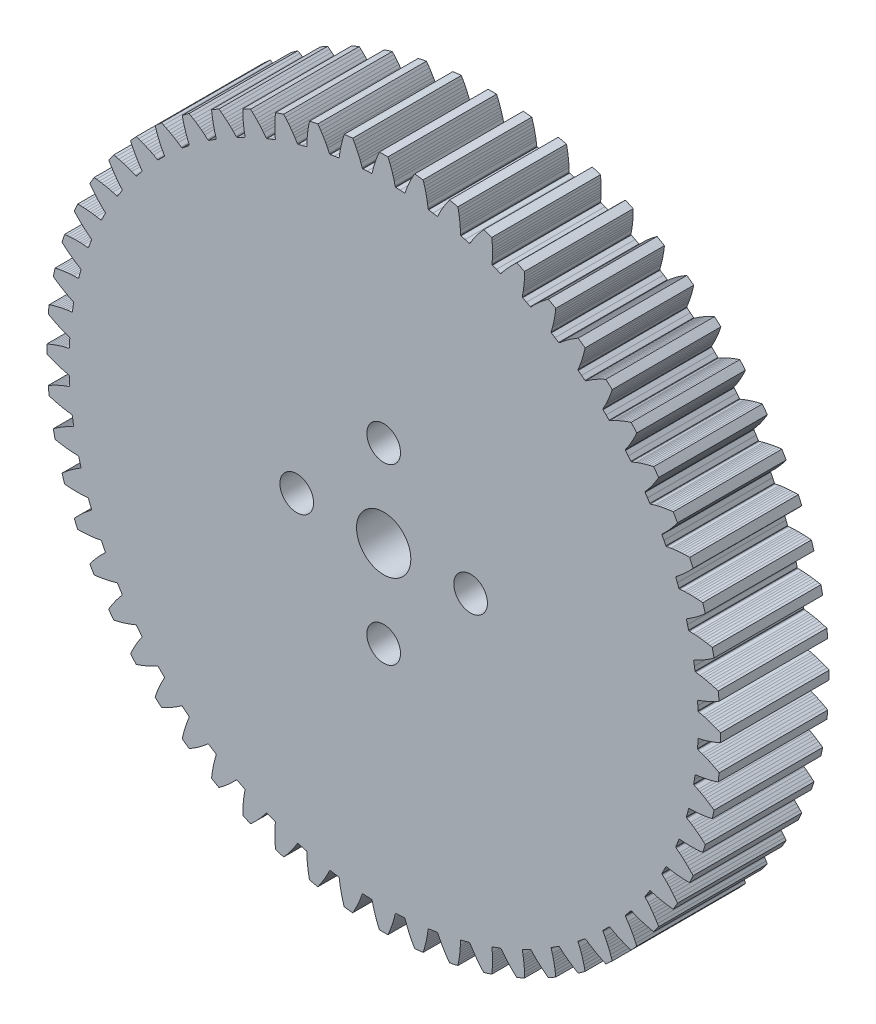
SolidWorks part; units mm, degrees
ref_plane "Front Plane" through (0, 0, 0) normal (0, 0, 1) x (1, 0, 0)
ref_plane "Top Plane" through (0, 0, 0) normal (0, 1, 0) x (1, 0, 0)
ref_plane "Right Plane" through (0, 0, 0) normal (1, 0, 0) x (0, 0, -1)
sketch "Model" plane through (0, 0, 0) normal (0, 0, 1) x (1, 0, 0)
  line L0 (30.676, 2.741) -> (30.453, 2.6211)
  line L1 (30.453, 2.6211) -> (30.2376, 2.5111)
  line L2 (30.2376, 2.5111) -> (30.0323, 2.4116)
  line L3 (30.0323, 2.4116) -> (29.8355, 2.3213)
  line L4 (29.8355, 2.3213) -> (29.6473, 2.2396)
  line L5 (29.6473, 2.2396) -> (29.4705, 2.1673)
  line L6 (29.4705, 2.1673) -> (29.3033, 2.1029)
  line L7 (29.3033, 2.1029) -> (28.9724, 1.9849)
  line L8 (28.9724, 1.9849) -> (28.931, 1.9629)
  line L9 (28.931, 1.9629) -> (28.9033, 1.9404)
  line L10 (28.9033, 1.9404) -> (28.8892, 1.9178)
  line L11 (28.8892, 1.9178) -> (28.8876, 1.9012)
  line L12 (28.8876, 1.9012) -> (28.9103, 1.5151)
  line L13 (28.9103, 1.5151) -> (28.9281, 1.1288)
  line L14 (28.9281, 1.1288) -> (28.9314, 1.1124)
  line L15 (28.9314, 1.1124) -> (28.9478, 1.0915)
  line L16 (28.9478, 1.0915) -> (28.9777, 1.0719)
  line L17 (28.9777, 1.0719) -> (29.0211, 1.0544)
  line L18 (29.0211, 1.0544) -> (29.3626, 0.9717)
  line L19 (29.3626, 0.9717) -> (29.5356, 0.9251)
  line L20 (29.5356, 0.9251) -> (29.719, 0.8717)
  line L21 (29.719, 0.8717) -> (29.9147, 0.8101)
  line L22 (29.9147, 0.8101) -> (30.1199, 0.7408)
  line L23 (30.1199, 0.7408) -> (30.3344, 0.6634)
  line L24 (30.3344, 0.6634) -> (30.5601, 0.5765)
  line L25 (30.5601, 0.5765) -> (30.7945, 0.4805)
  line L26 (30.7945, 0.4805) -> (30.9975, 0.3928)
  line L27 (30.9975, -0.3928) -> (30.7945, -0.4805)
  line L28 (30.7945, -0.4805) -> (30.5601, -0.5765)
  line L29 (30.5601, -0.5765) -> (30.3344, -0.6634)
  line L30 (30.3344, -0.6634) -> (30.1199, -0.7408)
  line L31 (30.1199, -0.7408) -> (29.9147, -0.8101)
  line L32 (29.9147, -0.8101) -> (29.719, -0.8717)
  line L33 (29.719, -0.8717) -> (29.5356, -0.9251)
  line L34 (29.5356, -0.9251) -> (29.3626, -0.9717)
  line L35 (29.3626, -0.9717) -> (29.0211, -1.0544)
  line L36 (29.0211, -1.0544) -> (28.9777, -1.0719)
  line L37 (28.9777, -1.0719) -> (28.9478, -1.0915)
  line L38 (28.9478, -1.0915) -> (28.9314, -1.1124)
  line L39 (28.9314, -1.1124) -> (28.9281, -1.1288)
  line L40 (28.9281, -1.1288) -> (28.9103, -1.5151)
  line L41 (28.9103, -1.5151) -> (28.8876, -1.9012)
  line L42 (28.8876, -1.9012) -> (28.8892, -1.9178)
  line L43 (28.8892, -1.9178) -> (28.9033, -1.9404)
  line L44 (28.9033, -1.9404) -> (28.931, -1.9629)
  line L45 (28.931, -1.9629) -> (28.9724, -1.9849)
  line L46 (28.9724, -1.9849) -> (29.3033, -2.1029)
  line L47 (29.3033, -2.1029) -> (29.4705, -2.1673)
  line L48 (29.4705, -2.1673) -> (29.6473, -2.2396)
  line L49 (29.6473, -2.2396) -> (29.8355, -2.3213)
  line L50 (29.8355, -2.3213) -> (30.0323, -2.4116)
  line L51 (30.0323, -2.4116) -> (30.2376, -2.5111)
  line L52 (30.2376, -2.5111) -> (30.453, -2.6211)
  line L53 (30.453, -2.6211) -> (30.676, -2.741)
  line L54 (30.676, -2.741) -> (30.8688, -2.8495)
  line L55 (30.7866, -3.6308) -> (30.5755, -3.6968)
  line L56 (30.5755, -3.6968) -> (30.3325, -3.7677)
  line L57 (30.3325, -3.7677) -> (30.0989, -3.8305)
  line L58 (30.0989, -3.8305) -> (29.8774, -3.8852)
  line L59 (29.8774, -3.8852) -> (29.6661, -3.9326)
  line L60 (29.6661, -3.9326) -> (29.465, -3.9734)
  line L61 (29.465, -3.9734) -> (29.2771, -4.0074)
  line L62 (29.2771, -4.0074) -> (29.1001, -4.0356)
  line L63 (29.1001, -4.0356) -> (28.7519, -4.0822)
  line L64 (28.7519, -4.0822) -> (28.7069, -4.0951)
  line L65 (28.7069, -4.0951) -> (28.6751, -4.1114)
  line L66 (28.6751, -4.1114) -> (28.6567, -4.1305)
  line L67 (28.6567, -4.1305) -> (28.6516, -4.1464)
  line L68 (28.6516, -4.1464) -> (28.5936, -4.5288)
  line L69 (28.5936, -4.5288) -> (28.5306, -4.9104)
  line L70 (28.5306, -4.9104) -> (28.5305, -4.927)
  line L71 (28.5305, -4.927) -> (28.5421, -4.951)
  line L72 (28.5421, -4.951) -> (28.5674, -4.9763)
  line L73 (28.5674, -4.9763) -> (28.6062, -5.0025)
  line L74 (28.6062, -5.0025) -> (28.9229, -5.1544)
  line L75 (28.9229, -5.1544) -> (29.0826, -5.2359)
  line L76 (29.0826, -5.2359) -> (29.2508, -5.3263)
  line L77 (29.2508, -5.3263) -> (29.4294, -5.4272)
  line L78 (29.4294, -5.4272) -> (29.6157, -5.5376)
  line L79 (29.6157, -5.5376) -> (29.8094, -5.658)
  line L80 (29.8094, -5.658) -> (30.0122, -5.79)
  line L81 (30.0122, -5.79) -> (30.2214, -5.9325)
  line L82 (30.2214, -5.9325) -> (30.4018, -6.0605)
  line L83 (30.2385, -6.829) -> (30.0216, -6.8726)
  line L84 (30.0216, -6.8726) -> (29.7725, -6.9177)
  line L85 (29.7725, -6.9177) -> (29.5336, -6.9557)
  line L86 (29.5336, -6.9557) -> (29.3077, -6.9869)
  line L87 (29.3077, -6.9869) -> (29.0926, -7.012)
  line L88 (29.0926, -7.012) -> (28.8883, -7.0315)
  line L89 (28.8883, -7.0315) -> (28.6979, -7.0457)
  line L90 (28.6979, -7.0457) -> (28.5189, -7.0553)
  line L91 (28.5189, -7.0553) -> (28.1677, -7.0652)
  line L92 (28.1677, -7.0652) -> (28.1216, -7.0733)
  line L93 (28.1216, -7.0733) -> (28.0883, -7.0862)
  line L94 (28.0883, -7.0862) -> (28.0679, -7.1033)
  line L95 (28.0679, -7.1033) -> (28.0612, -7.1186)
  line L96 (28.0612, -7.1186) -> (27.9636, -7.4928)
  line L97 (27.9636, -7.4928) -> (27.861, -7.8657)
  line L98 (27.861, -7.8657) -> (27.8592, -7.8823)
  line L99 (27.8592, -7.8823) -> (27.8683, -7.9073)
  line L100 (27.8683, -7.9073) -> (27.8907, -7.9351)
  line L101 (27.8907, -7.9351) -> (27.9266, -7.9652)
  line L102 (27.9266, -7.9652) -> (28.2257, -8.1494)
  line L103 (28.2257, -8.1494) -> (28.3759, -8.2472)
  line L104 (28.3759, -8.2472) -> (28.5338, -8.3547)
  line L105 (28.5338, -8.3547) -> (28.7009, -8.4737)
  line L106 (28.7009, -8.4737) -> (28.8746, -8.603)
  line L107 (28.8746, -8.603) -> (29.0547, -8.7429)
  line L108 (29.0547, -8.7429) -> (29.2425, -8.8954)
  line L109 (29.2425, -8.8954) -> (29.4358, -9.059)
  line L110 (29.4358, -9.059) -> (29.6018, -9.2052)
  line L111 (29.359, -9.9523) -> (29.1388, -9.973)
  line L112 (29.1388, -9.973) -> (28.8863, -9.9918)
  line L113 (28.8863, -9.9918) -> (28.6447, -10.0047)
  line L114 (28.6447, -10.0047) -> (28.4168, -10.0121)
  line L115 (28.4168, -10.0121) -> (28.2002, -10.0146)
  line L116 (28.2002, -10.0146) -> (27.995, -10.0127)
  line L117 (27.995, -10.0127) -> (27.8042, -10.0069)
  line L118 (27.8042, -10.0069) -> (27.6252, -9.9977)
  line L119 (27.6252, -9.9977) -> (27.2749, -9.9708)
  line L120 (27.2749, -9.9708) -> (27.2282, -9.9741)
  line L121 (27.2282, -9.9741) -> (27.1937, -9.9834)
  line L122 (27.1937, -9.9834) -> (27.1717, -9.9983)
  line L123 (27.1717, -9.9983) -> (27.1634, -10.0128)
  line L124 (27.1634, -10.0128) -> (27.0272, -10.3748)
  line L125 (27.0272, -10.3748) -> (26.8862, -10.7349)
  line L126 (26.8862, -10.7349) -> (26.8826, -10.7512)
  line L127 (26.8826, -10.7512) -> (26.8891, -10.777)
  line L128 (26.8891, -10.777) -> (26.9085, -10.807)
  line L129 (26.9085, -10.807) -> (26.941, -10.8407)
  line L130 (26.941, -10.8407) -> (27.2193, -11.0551)
  line L131 (27.2193, -11.0551) -> (27.3584, -11.1681)
  line L132 (27.3584, -11.1681) -> (27.5042, -11.2915)
  line L133 (27.5042, -11.2915) -> (27.6579, -11.4273)
  line L134 (27.6579, -11.4273) -> (27.8172, -11.5741)
  line L135 (27.8172, -11.5741) -> (27.9817, -11.7321)
  line L136 (27.9817, -11.7321) -> (28.1525, -11.9033)
  line L137 (28.1525, -11.9033) -> (28.3276, -12.0862)
  line L138 (28.3276, -12.0862) -> (28.4774, -12.249)
  line L139 (28.1579, -12.9667) -> (27.9367, -12.9642)
  line L140 (27.9367, -12.9642) -> (27.6836, -12.9565)
  line L141 (27.6836, -12.9565) -> (27.442, -12.9441)
  line L142 (27.442, -12.9441) -> (27.2145, -12.9276)
  line L143 (27.2145, -12.9276) -> (26.9989, -12.9075)
  line L144 (26.9989, -12.9075) -> (26.7951, -12.8841)
  line L145 (26.7951, -12.8841) -> (26.6059, -12.8584)
  line L146 (26.6059, -12.8584) -> (26.4288, -12.8305)
  line L147 (26.4288, -12.8305) -> (26.0833, -12.7672)
  line L148 (26.0833, -12.7672) -> (26.0365, -12.7656)
  line L149 (26.0365, -12.7656) -> (26.0012, -12.7712)
  line L150 (26.0012, -12.7712) -> (25.9777, -12.7837)
  line L151 (25.9777, -12.7837) -> (25.968, -12.7973)
  line L152 (25.968, -12.7973) -> (25.7946, -13.143)
  line L153 (25.7946, -13.143) -> (25.6168, -13.4865)
  line L154 (25.6168, -13.4865) -> (25.6116, -13.5023)
  line L155 (25.6116, -13.5023) -> (25.6153, -13.5287)
  line L156 (25.6153, -13.5287) -> (25.6314, -13.5605)
  line L157 (25.6314, -13.5605) -> (25.6603, -13.5974)
  line L158 (25.6603, -13.5974) -> (25.9146, -13.8398)
  line L159 (25.9146, -13.8398) -> (26.0412, -13.9666)
  line L160 (26.0412, -13.9666) -> (26.1732, -14.1046)
  line L161 (26.1732, -14.1046) -> (26.312, -14.2558)
  line L162 (26.312, -14.2558) -> (26.455, -14.4184)
  line L163 (26.455, -14.4184) -> (26.602, -14.5927)
  line L164 (26.602, -14.5927) -> (26.7541, -14.7808)
  line L165 (26.7541, -14.7808) -> (26.9091, -14.9811)
  line L166 (26.9091, -14.9811) -> (27.041, -15.1586)
  line L167 (26.6482, -15.8389) -> (26.4285, -15.8134)
  line L168 (26.4285, -15.8134) -> (26.1776, -15.7793)
  line L169 (26.1776, -15.7793) -> (25.9387, -15.7417)
  line L170 (25.9387, -15.7417) -> (25.7142, -15.7015)
  line L171 (25.7142, -15.7015) -> (25.5018, -15.6589)
  line L172 (25.5018, -15.6589) -> (25.3015, -15.6144)
  line L173 (25.3015, -15.6144) -> (25.1161, -15.569)
  line L174 (25.1161, -15.569) -> (24.9429, -15.5228)
  line L175 (24.9429, -15.5228) -> (24.6058, -15.4237)
  line L176 (24.6058, -15.4237) -> (24.5595, -15.4172)
  line L177 (24.5595, -15.4172) -> (24.5238, -15.4191)
  line L178 (24.5238, -15.4191) -> (24.4991, -15.4291)
  line L179 (24.4991, -15.4291) -> (24.488, -15.4416)
  line L180 (24.488, -15.4416) -> (24.2795, -15.7673)
  line L181 (24.2795, -15.7673) -> (24.0668, -16.0903)
  line L182 (24.0668, -16.0903) -> (24.0599, -16.1055)
  line L183 (24.0599, -16.1055) -> (24.0608, -16.1321)
  line L184 (24.0608, -16.1321) -> (24.0735, -16.1655)
  line L185 (24.0735, -16.1655) -> (24.0984, -16.2052)
  line L186 (24.0984, -16.2052) -> (24.326, -16.4728)
  line L187 (24.326, -16.4728) -> (24.4386, -16.6122)
  line L188 (24.4386, -16.6122) -> (24.5555, -16.7632)
  line L189 (24.5555, -16.7632) -> (24.6777, -16.928)
  line L190 (24.6777, -16.928) -> (24.8029, -17.1047)
  line L191 (24.8029, -17.1047) -> (24.931, -17.2934)
  line L192 (24.931, -17.2934) -> (25.0625, -17.4964)
  line L193 (25.0625, -17.4964) -> (25.1957, -17.7118)
  line L194 (25.1957, -17.7118) -> (25.3084, -17.9021)
  line L195 (24.8466, -18.5377) -> (24.6308, -18.4893)
  line L196 (24.6308, -18.4893) -> (24.3848, -18.4292)
  line L197 (24.3848, -18.4292) -> (24.1511, -18.3668)
  line L198 (24.1511, -18.3668) -> (23.932, -18.3034)
  line L199 (23.932, -18.3034) -> (23.7253, -18.2388)
  line L200 (23.7253, -18.2388) -> (23.5308, -18.1736)
  line L201 (23.5308, -18.1736) -> (23.3511, -18.1091)
  line L202 (23.3511, -18.1091) -> (23.1837, -18.045)
  line L203 (23.1837, -18.045) -> (22.8588, -17.9112)
  line L204 (22.8588, -17.9112) -> (22.8134, -17.8999)
  line L205 (22.8134, -17.8999) -> (22.7777, -17.8981)
  line L206 (22.7777, -17.8981) -> (22.7521, -17.9055)
  line L207 (22.7521, -17.9055) -> (22.7398, -17.9167)
  line L208 (22.7398, -17.9167) -> (22.4984, -18.2188)
  line L209 (22.4984, -18.2188) -> (22.2531, -18.5178)
  line L210 (22.2531, -18.5178) -> (22.2446, -18.5322)
  line L211 (22.2446, -18.5322) -> (22.2427, -18.5587)
  line L212 (22.2427, -18.5587) -> (22.2519, -18.5933)
  line L213 (22.2519, -18.5933) -> (22.2724, -18.6353)
  line L214 (22.2724, -18.6353) -> (22.4708, -18.9253)
  line L215 (22.4708, -18.9253) -> (22.5683, -19.0757)
  line L216 (22.5683, -19.0757) -> (22.6688, -19.2381)
  line L217 (22.6688, -19.2381) -> (22.773, -19.4148)
  line L218 (22.773, -19.4148) -> (22.8791, -19.6036)
  line L219 (22.8791, -19.6036) -> (22.9867, -19.8047)
  line L220 (22.9867, -19.8047) -> (23.0963, -20.0203)
  line L221 (23.0963, -20.0203) -> (23.2063, -20.2484)
  line L222 (23.2063, -20.2484) -> (23.2985, -20.4495)
  line L223 (22.7728, -21.0333) -> (22.5632, -20.9626)
  line L224 (22.5632, -20.9626) -> (22.3249, -20.8771)
  line L225 (22.3249, -20.8771) -> (22.099, -20.7906)
  line L226 (22.099, -20.7906) -> (21.8877, -20.7047)
  line L227 (21.8877, -20.7047) -> (21.6889, -20.6189)
  line L228 (21.6889, -20.6189) -> (21.5022, -20.5336)
  line L229 (21.5022, -20.5336) -> (21.3302, -20.4507)
  line L230 (21.3302, -20.4507) -> (21.1705, -20.3695)
  line L231 (21.1705, -20.3695) -> (20.8614, -20.2025)
  line L232 (20.8614, -20.2025) -> (20.8174, -20.1865)
  line L233 (20.8174, -20.1865) -> (20.7821, -20.181)
  line L234 (20.7821, -20.181) -> (20.7559, -20.1856)
  line L235 (20.7559, -20.1856) -> (20.7424, -20.1955)
  line L236 (20.7424, -20.1955) -> (20.4707, -20.4707)
  line L237 (20.4707, -20.4707) -> (20.1955, -20.7424)
  line L238 (20.1955, -20.7424) -> (20.1856, -20.7559)
  line L239 (20.1856, -20.7559) -> (20.181, -20.7821)
  line L240 (20.181, -20.7821) -> (20.1865, -20.8174)
  line L241 (20.1865, -20.8174) -> (20.2025, -20.8614)
  line L242 (20.2025, -20.8614) -> (20.3695, -21.1705)
  line L243 (20.3695, -21.1705) -> (20.4507, -21.3302)
  line L244 (20.4507, -21.3302) -> (20.5336, -21.5022)
  line L245 (20.5336, -21.5022) -> (20.6189, -21.6889)
  line L246 (20.6189, -21.6889) -> (20.7047, -21.8877)
  line L247 (20.7047, -21.8877) -> (20.7906, -22.099)
  line L248 (20.7906, -22.099) -> (20.8771, -22.3249)
  line L249 (20.8771, -22.3249) -> (20.9626, -22.5632)
  line L250 (20.9626, -22.5632) -> (21.0333, -22.7728)
  line L251 (20.4495, -23.2985) -> (20.2484, -23.2063)
  line L252 (20.2484, -23.2063) -> (20.0203, -23.0963)
  line L253 (20.0203, -23.0963) -> (19.8047, -22.9867)
  line L254 (19.8047, -22.9867) -> (19.6036, -22.8791)
  line L255 (19.6036, -22.8791) -> (19.4148, -22.773)
  line L256 (19.4148, -22.773) -> (19.2381, -22.6688)
  line L257 (19.2381, -22.6688) -> (19.0757, -22.5683)
  line L258 (19.0757, -22.5683) -> (18.9253, -22.4708)
  line L259 (18.9253, -22.4708) -> (18.6353, -22.2724)
  line L260 (18.6353, -22.2724) -> (18.5933, -22.2519)
  line L261 (18.5933, -22.2519) -> (18.5587, -22.2427)
  line L262 (18.5587, -22.2427) -> (18.5322, -22.2446)
  line L263 (18.5322, -22.2446) -> (18.5178, -22.2531)
  line L264 (18.5178, -22.2531) -> (18.2188, -22.4984)
  line L265 (18.2188, -22.4984) -> (17.9167, -22.7398)
  line L266 (17.9167, -22.7398) -> (17.9055, -22.7521)
  line L267 (17.9055, -22.7521) -> (17.8981, -22.7777)
  line L268 (17.8981, -22.7777) -> (17.8999, -22.8134)
  line L269 (17.8999, -22.8134) -> (17.9112, -22.8588)
  line L270 (17.9112, -22.8588) -> (18.045, -23.1837)
  line L271 (18.045, -23.1837) -> (18.1091, -23.3511)
  line L272 (18.1091, -23.3511) -> (18.1736, -23.5308)
  line L273 (18.1736, -23.5308) -> (18.2388, -23.7253)
  line L274 (18.2388, -23.7253) -> (18.3034, -23.932)
  line L275 (18.3034, -23.932) -> (18.3668, -24.1511)
  line L276 (18.3668, -24.1511) -> (18.4292, -24.3848)
  line L277 (18.4292, -24.3848) -> (18.4893, -24.6308)
  line L278 (18.4893, -24.6308) -> (18.5377, -24.8466)
  line L279 (17.9021, -25.3084) -> (17.7118, -25.1957)
  line L280 (17.7118, -25.1957) -> (17.4964, -25.0625)
  line L281 (17.4964, -25.0625) -> (17.2934, -24.931)
  line L282 (17.2934, -24.931) -> (17.1047, -24.8029)
  line L283 (17.1047, -24.8029) -> (16.928, -24.6777)
  line L284 (16.928, -24.6777) -> (16.7632, -24.5555)
  line L285 (16.7632, -24.5555) -> (16.6122, -24.4386)
  line L286 (16.6122, -24.4386) -> (16.4728, -24.326)
  line L287 (16.4728, -24.326) -> (16.2052, -24.0984)
  line L288 (16.2052, -24.0984) -> (16.1655, -24.0735)
  line L289 (16.1655, -24.0735) -> (16.1321, -24.0608)
  line L290 (16.1321, -24.0608) -> (16.1055, -24.0599)
  line L291 (16.1055, -24.0599) -> (16.0903, -24.0668)
  line L292 (16.0903, -24.0668) -> (15.7673, -24.2795)
  line L293 (15.7673, -24.2795) -> (15.4416, -24.488)
  line L294 (15.4416, -24.488) -> (15.4291, -24.4991)
  line L295 (15.4291, -24.4991) -> (15.4191, -24.5238)
  line L296 (15.4191, -24.5238) -> (15.4172, -24.5595)
  line L297 (15.4172, -24.5595) -> (15.4237, -24.6058)
  line L298 (15.4237, -24.6058) -> (15.5228, -24.9429)
  line L299 (15.5228, -24.9429) -> (15.569, -25.1161)
  line L300 (15.569, -25.1161) -> (15.6144, -25.3015)
  line L301 (15.6144, -25.3015) -> (15.6589, -25.5018)
  line L302 (15.6589, -25.5018) -> (15.7015, -25.7142)
  line L303 (15.7015, -25.7142) -> (15.7417, -25.9387)
  line L304 (15.7417, -25.9387) -> (15.7793, -26.1776)
  line L305 (15.7793, -26.1776) -> (15.8134, -26.4285)
  line L306 (15.8134, -26.4285) -> (15.8389, -26.6482)
  line L307 (15.1586, -27.041) -> (14.9811, -26.9091)
  line L308 (14.9811, -26.9091) -> (14.7808, -26.7541)
  line L309 (14.7808, -26.7541) -> (14.5927, -26.602)
  line L310 (14.5927, -26.602) -> (14.4184, -26.455)
  line L311 (14.4184, -26.455) -> (14.2558, -26.312)
  line L312 (14.2558, -26.312) -> (14.1046, -26.1732)
  line L313 (14.1046, -26.1732) -> (13.9666, -26.0412)
  line L314 (13.9666, -26.0412) -> (13.8398, -25.9146)
  line L315 (13.8398, -25.9146) -> (13.5974, -25.6603)
  line L316 (13.5974, -25.6603) -> (13.5605, -25.6314)
  line L317 (13.5605, -25.6314) -> (13.5287, -25.6153)
  line L318 (13.5287, -25.6153) -> (13.5023, -25.6116)
  line L319 (13.5023, -25.6116) -> (13.4865, -25.6168)
  line L320 (13.4865, -25.6168) -> (13.143, -25.7946)
  line L321 (13.143, -25.7946) -> (12.7973, -25.968)
  line L322 (12.7973, -25.968) -> (12.7837, -25.9777)
  line L323 (12.7837, -25.9777) -> (12.7712, -26.0012)
  line L324 (12.7712, -26.0012) -> (12.7656, -26.0365)
  line L325 (12.7656, -26.0365) -> (12.7672, -26.0833)
  line L326 (12.7672, -26.0833) -> (12.8305, -26.4288)
  line L327 (12.8305, -26.4288) -> (12.8584, -26.6059)
  line L328 (12.8584, -26.6059) -> (12.8841, -26.7951)
  line L329 (12.8841, -26.7951) -> (12.9075, -26.9989)
  line L330 (12.9075, -26.9989) -> (12.9276, -27.2145)
  line L331 (12.9276, -27.2145) -> (12.9441, -27.442)
  line L332 (12.9441, -27.442) -> (12.9565, -27.6836)
  line L333 (12.9565, -27.6836) -> (12.9642, -27.9367)
  line L334 (12.9642, -27.9367) -> (12.9667, -28.1579)
  line L335 (12.249, -28.4774) -> (12.0862, -28.3276)
  line L336 (12.0862, -28.3276) -> (11.9033, -28.1525)
  line L337 (11.9033, -28.1525) -> (11.7321, -27.9817)
  line L338 (11.7321, -27.9817) -> (11.5741, -27.8172)
  line L339 (11.5741, -27.8172) -> (11.4273, -27.6579)
  line L340 (11.4273, -27.6579) -> (11.2915, -27.5042)
  line L341 (11.2915, -27.5042) -> (11.1681, -27.3584)
  line L342 (11.1681, -27.3584) -> (11.0551, -27.2193)
  line L343 (11.0551, -27.2193) -> (10.8407, -26.941)
  line L344 (10.8407, -26.941) -> (10.807, -26.9085)
  line L345 (10.807, -26.9085) -> (10.777, -26.8891)
  line L346 (10.777, -26.8891) -> (10.7512, -26.8826)
  line L347 (10.7512, -26.8826) -> (10.7349, -26.8862)
  line L348 (10.7349, -26.8862) -> (10.3748, -27.0272)
  line L349 (10.3748, -27.0272) -> (10.0128, -27.1634)
  line L350 (10.0128, -27.1634) -> (9.9983, -27.1717)
  line L351 (9.9983, -27.1717) -> (9.9834, -27.1937)
  line L352 (9.9834, -27.1937) -> (9.9741, -27.2282)
  line L353 (9.9741, -27.2282) -> (9.9708, -27.2749)
  line L354 (9.9708, -27.2749) -> (9.9977, -27.6252)
  line L355 (9.9977, -27.6252) -> (10.0069, -27.8042)
  line L356 (10.0069, -27.8042) -> (10.0127, -27.995)
  line L357 (10.0127, -27.995) -> (10.0146, -28.2002)
  line L358 (10.0146, -28.2002) -> (10.0121, -28.4168)
  line L359 (10.0121, -28.4168) -> (10.0047, -28.6447)
  line L360 (10.0047, -28.6447) -> (9.9918, -28.8863)
  line L361 (9.9918, -28.8863) -> (9.973, -29.1388)
  line L362 (9.973, -29.1388) -> (9.9523, -29.359)
  line L363 (9.2052, -29.6018) -> (9.059, -29.4358)
  line L364 (9.059, -29.4358) -> (8.8954, -29.2425)
  line L365 (8.8954, -29.2425) -> (8.7429, -29.0547)
  line L366 (8.7429, -29.0547) -> (8.603, -28.8746)
  line L367 (8.603, -28.8746) -> (8.4737, -28.7009)
  line L368 (8.4737, -28.7009) -> (8.3547, -28.5338)
  line L369 (8.3547, -28.5338) -> (8.2472, -28.3759)
  line L370 (8.2472, -28.3759) -> (8.1494, -28.2257)
  line L371 (8.1494, -28.2257) -> (7.9652, -27.9266)
  line L372 (7.9652, -27.9266) -> (7.9351, -27.8907)
  line L373 (7.9351, -27.8907) -> (7.9073, -27.8683)
  line L374 (7.9073, -27.8683) -> (7.8823, -27.8592)
  line L375 (7.8823, -27.8592) -> (7.8657, -27.861)
  line L376 (7.8657, -27.861) -> (7.4928, -27.9636)
  line L377 (7.4928, -27.9636) -> (7.1186, -28.0612)
  line L378 (7.1186, -28.0612) -> (7.1033, -28.0679)
  line L379 (7.1033, -28.0679) -> (7.0862, -28.0883)
  line L380 (7.0862, -28.0883) -> (7.0733, -28.1216)
  line L381 (7.0733, -28.1216) -> (7.0652, -28.1677)
  line L382 (7.0652, -28.1677) -> (7.0553, -28.5189)
  line L383 (7.0553, -28.5189) -> (7.0457, -28.6979)
  line L384 (7.0457, -28.6979) -> (7.0315, -28.8883)
  line L385 (7.0315, -28.8883) -> (7.012, -29.0926)
  line L386 (7.012, -29.0926) -> (6.9869, -29.3077)
  line L387 (6.9869, -29.3077) -> (6.9557, -29.5336)
  line L388 (6.9557, -29.5336) -> (6.9177, -29.7725)
  line L389 (6.9177, -29.7725) -> (6.8726, -30.0216)
  line L390 (6.8726, -30.0216) -> (6.829, -30.2385)
  line L391 (6.0605, -30.4018) -> (5.9325, -30.2214)
  line L392 (5.9325, -30.2214) -> (5.79, -30.0122)
  line L393 (5.79, -30.0122) -> (5.658, -29.8094)
  line L394 (5.658, -29.8094) -> (5.5376, -29.6157)
  line L395 (5.5376, -29.6157) -> (5.4272, -29.4294)
  line L396 (5.4272, -29.4294) -> (5.3263, -29.2508)
  line L397 (5.3263, -29.2508) -> (5.2359, -29.0826)
  line L398 (5.2359, -29.0826) -> (5.1544, -28.9229)
  line L399 (5.1544, -28.9229) -> (5.0025, -28.6062)
  line L400 (5.0025, -28.6062) -> (4.9763, -28.5674)
  line L401 (4.9763, -28.5674) -> (4.951, -28.5421)
  line L402 (4.951, -28.5421) -> (4.927, -28.5305)
  line L403 (4.927, -28.5305) -> (4.9104, -28.5306)
  line L404 (4.9104, -28.5306) -> (4.5288, -28.5936)
  line L405 (4.5288, -28.5936) -> (4.1464, -28.6516)
  line L406 (4.1464, -28.6516) -> (4.1305, -28.6567)
  line L407 (4.1305, -28.6567) -> (4.1114, -28.6751)
  line L408 (4.1114, -28.6751) -> (4.0951, -28.7069)
  line L409 (4.0951, -28.7069) -> (4.0822, -28.7519)
  line L410 (4.0822, -28.7519) -> (4.0356, -29.1001)
  line L411 (4.0356, -29.1001) -> (4.0074, -29.2771)
  line L412 (4.0074, -29.2771) -> (3.9734, -29.465)
  line L413 (3.9734, -29.465) -> (3.9326, -29.6661)
  line L414 (3.9326, -29.6661) -> (3.8852, -29.8774)
  line L415 (3.8852, -29.8774) -> (3.8305, -30.0989)
  line L416 (3.8305, -30.0989) -> (3.7677, -30.3325)
  line L417 (3.7677, -30.3325) -> (3.6968, -30.5755)
  line L418 (3.6968, -30.5755) -> (3.6308, -30.7866)
  line L419 (2.8495, -30.8688) -> (2.741, -30.676)
  line L420 (2.741, -30.676) -> (2.6211, -30.453)
  line L421 (2.6211, -30.453) -> (2.5111, -30.2376)
  line L422 (2.5111, -30.2376) -> (2.4116, -30.0323)
  line L423 (2.4116, -30.0323) -> (2.3213, -29.8355)
  line L424 (2.3213, -29.8355) -> (2.2396, -29.6473)
  line L425 (2.2396, -29.6473) -> (2.1673, -29.4705)
  line L426 (2.1673, -29.4705) -> (2.1029, -29.3033)
  line L427 (2.1029, -29.3033) -> (1.9849, -28.9724)
  line L428 (1.9849, -28.9724) -> (1.9629, -28.931)
  line L429 (1.9629, -28.931) -> (1.9404, -28.9033)
  line L430 (1.9404, -28.9033) -> (1.9178, -28.8892)
  line L431 (1.9178, -28.8892) -> (1.9012, -28.8876)
  line L432 (1.9012, -28.8876) -> (1.5151, -28.9103)
  line L433 (1.5151, -28.9103) -> (1.1288, -28.9281)
  line L434 (1.1288, -28.9281) -> (1.1124, -28.9314)
  line L435 (1.1124, -28.9314) -> (1.0915, -28.9478)
  line L436 (1.0915, -28.9478) -> (1.0719, -28.9777)
  line L437 (1.0719, -28.9777) -> (1.0544, -29.0211)
  line L438 (1.0544, -29.0211) -> (0.9717, -29.3626)
  line L439 (0.9717, -29.3626) -> (0.9251, -29.5356)
  line L440 (0.9251, -29.5356) -> (0.8717, -29.719)
  line L441 (0.8717, -29.719) -> (0.8101, -29.9147)
  line L442 (0.8101, -29.9147) -> (0.7408, -30.1199)
  line L443 (0.7408, -30.1199) -> (0.6634, -30.3344)
  line L444 (0.6634, -30.3344) -> (0.5765, -30.5601)
  line L445 (0.5765, -30.5601) -> (0.4805, -30.7945)
  line L446 (0.4805, -30.7945) -> (0.3928, -30.9975)
  line L447 (-0.3928, -30.9975) -> (-0.4805, -30.7945)
  line L448 (-0.4805, -30.7945) -> (-0.5765, -30.5601)
  line L449 (-0.5765, -30.5601) -> (-0.6634, -30.3344)
  line L450 (-0.6634, -30.3344) -> (-0.7408, -30.1199)
  line L451 (-0.7408, -30.1199) -> (-0.8101, -29.9147)
  line L452 (-0.8101, -29.9147) -> (-0.8717, -29.719)
  line L453 (-0.8717, -29.719) -> (-0.9251, -29.5356)
  line L454 (-0.9251, -29.5356) -> (-0.9717, -29.3626)
  line L455 (-0.9717, -29.3626) -> (-1.0544, -29.0211)
  line L456 (-1.0544, -29.0211) -> (-1.0719, -28.9777)
  line L457 (-1.0719, -28.9777) -> (-1.0915, -28.9478)
  line L458 (-1.0915, -28.9478) -> (-1.1124, -28.9314)
  line L459 (-1.1124, -28.9314) -> (-1.1288, -28.9281)
  line L460 (-1.1288, -28.9281) -> (-1.5151, -28.9103)
  line L461 (-1.5151, -28.9103) -> (-1.9012, -28.8876)
  line L462 (-1.9012, -28.8876) -> (-1.9178, -28.8892)
  line L463 (-1.9178, -28.8892) -> (-1.9404, -28.9033)
  line L464 (-1.9404, -28.9033) -> (-1.9629, -28.931)
  line L465 (-1.9629, -28.931) -> (-1.9849, -28.9724)
  line L466 (-1.9849, -28.9724) -> (-2.1029, -29.3033)
  line L467 (-2.1029, -29.3033) -> (-2.1673, -29.4705)
  line L468 (-2.1673, -29.4705) -> (-2.2396, -29.6473)
  line L469 (-2.2396, -29.6473) -> (-2.3213, -29.8355)
  line L470 (-2.3213, -29.8355) -> (-2.4116, -30.0323)
  line L471 (-2.4116, -30.0323) -> (-2.5111, -30.2376)
  line L472 (-2.5111, -30.2376) -> (-2.6211, -30.453)
  line L473 (-2.6211, -30.453) -> (-2.741, -30.676)
  line L474 (-2.741, -30.676) -> (-2.8495, -30.8688)
  line L475 (-3.6308, -30.7866) -> (-3.6968, -30.5755)
  line L476 (-3.6968, -30.5755) -> (-3.7677, -30.3325)
  line L477 (-3.7677, -30.3325) -> (-3.8305, -30.0989)
  line L478 (-3.8305, -30.0989) -> (-3.8852, -29.8774)
  line L479 (-3.8852, -29.8774) -> (-3.9326, -29.6661)
  line L480 (-3.9326, -29.6661) -> (-3.9734, -29.465)
  line L481 (-3.9734, -29.465) -> (-4.0074, -29.2771)
  line L482 (-4.0074, -29.2771) -> (-4.0356, -29.1001)
  line L483 (-4.0356, -29.1001) -> (-4.0822, -28.7519)
  line L484 (-4.0822, -28.7519) -> (-4.0951, -28.7069)
  line L485 (-4.0951, -28.7069) -> (-4.1114, -28.6751)
  line L486 (-4.1114, -28.6751) -> (-4.1305, -28.6567)
  line L487 (-4.1305, -28.6567) -> (-4.1464, -28.6516)
  line L488 (-4.1464, -28.6516) -> (-4.5288, -28.5936)
  line L489 (-4.5288, -28.5936) -> (-4.9104, -28.5306)
  line L490 (-4.9104, -28.5306) -> (-4.927, -28.5305)
  line L491 (-4.927, -28.5305) -> (-4.951, -28.5421)
  line L492 (-4.951, -28.5421) -> (-4.9763, -28.5674)
  line L493 (-4.9763, -28.5674) -> (-5.0025, -28.6062)
  line L494 (-5.0025, -28.6062) -> (-5.1544, -28.9229)
  line L495 (-5.1544, -28.9229) -> (-5.2359, -29.0826)
  line L496 (-5.2359, -29.0826) -> (-5.3263, -29.2508)
  line L497 (-5.3263, -29.2508) -> (-5.4272, -29.4294)
  line L498 (-5.4272, -29.4294) -> (-5.5376, -29.6157)
  line L499 (-5.5376, -29.6157) -> (-5.658, -29.8094)
  line L500 (-5.658, -29.8094) -> (-5.79, -30.0122)
  line L501 (-5.79, -30.0122) -> (-5.9325, -30.2214)
  line L502 (-5.9325, -30.2214) -> (-6.0605, -30.4018)
  line L503 (-6.829, -30.2385) -> (-6.8726, -30.0216)
  line L504 (-6.8726, -30.0216) -> (-6.9177, -29.7725)
  line L505 (-6.9177, -29.7725) -> (-6.9557, -29.5336)
  line L506 (-6.9557, -29.5336) -> (-6.9869, -29.3077)
  line L507 (-6.9869, -29.3077) -> (-7.012, -29.0926)
  line L508 (-7.012, -29.0926) -> (-7.0315, -28.8883)
  line L509 (-7.0315, -28.8883) -> (-7.0457, -28.6979)
  line L510 (-7.0457, -28.6979) -> (-7.0553, -28.5189)
  line L511 (-7.0553, -28.5189) -> (-7.0652, -28.1677)
  line L512 (-7.0652, -28.1677) -> (-7.0733, -28.1216)
  line L513 (-7.0733, -28.1216) -> (-7.0862, -28.0883)
  line L514 (-7.0862, -28.0883) -> (-7.1033, -28.0679)
  line L515 (-7.1033, -28.0679) -> (-7.1186, -28.0612)
  line L516 (-7.1186, -28.0612) -> (-7.4928, -27.9636)
  line L517 (-7.4928, -27.9636) -> (-7.8657, -27.861)
  line L518 (-7.8657, -27.861) -> (-7.8823, -27.8592)
  line L519 (-7.8823, -27.8592) -> (-7.9073, -27.8683)
  line L520 (-7.9073, -27.8683) -> (-7.9351, -27.8907)
  line L521 (-7.9351, -27.8907) -> (-7.9652, -27.9266)
  line L522 (-7.9652, -27.9266) -> (-8.1494, -28.2257)
  line L523 (-8.1494, -28.2257) -> (-8.2472, -28.3759)
  line L524 (-8.2472, -28.3759) -> (-8.3547, -28.5338)
  line L525 (-8.3547, -28.5338) -> (-8.4737, -28.7009)
  line L526 (-8.4737, -28.7009) -> (-8.603, -28.8746)
  line L527 (-8.603, -28.8746) -> (-8.7429, -29.0547)
  line L528 (-8.7429, -29.0547) -> (-8.8954, -29.2425)
  line L529 (-8.8954, -29.2425) -> (-9.059, -29.4358)
  line L530 (-9.059, -29.4358) -> (-9.2052, -29.6018)
  line L531 (-9.9523, -29.359) -> (-9.973, -29.1388)
  line L532 (-9.973, -29.1388) -> (-9.9918, -28.8863)
  line L533 (-9.9918, -28.8863) -> (-10.0047, -28.6447)
  line L534 (-10.0047, -28.6447) -> (-10.0121, -28.4168)
  line L535 (-10.0121, -28.4168) -> (-10.0146, -28.2002)
  line L536 (-10.0146, -28.2002) -> (-10.0127, -27.995)
  line L537 (-10.0127, -27.995) -> (-10.0069, -27.8042)
  line L538 (-10.0069, -27.8042) -> (-9.9977, -27.6252)
  line L539 (-9.9977, -27.6252) -> (-9.9708, -27.2749)
  line L540 (-9.9708, -27.2749) -> (-9.9741, -27.2282)
  line L541 (-9.9741, -27.2282) -> (-9.9834, -27.1937)
  line L542 (-9.9834, -27.1937) -> (-9.9983, -27.1717)
  line L543 (-9.9983, -27.1717) -> (-10.0128, -27.1634)
  line L544 (-10.0128, -27.1634) -> (-10.3748, -27.0272)
  line L545 (-10.3748, -27.0272) -> (-10.7349, -26.8862)
  line L546 (-10.7349, -26.8862) -> (-10.7512, -26.8826)
  line L547 (-10.7512, -26.8826) -> (-10.777, -26.8891)
  line L548 (-10.777, -26.8891) -> (-10.807, -26.9085)
  line L549 (-10.807, -26.9085) -> (-10.8407, -26.941)
  line L550 (-10.8407, -26.941) -> (-11.0551, -27.2193)
  line L551 (-11.0551, -27.2193) -> (-11.1681, -27.3584)
  line L552 (-11.1681, -27.3584) -> (-11.2915, -27.5042)
  line L553 (-11.2915, -27.5042) -> (-11.4273, -27.6579)
  line L554 (-11.4273, -27.6579) -> (-11.5741, -27.8172)
  line L555 (-11.5741, -27.8172) -> (-11.7321, -27.9817)
  line L556 (-11.7321, -27.9817) -> (-11.9033, -28.1525)
  line L557 (-11.9033, -28.1525) -> (-12.0862, -28.3276)
  line L558 (-12.0862, -28.3276) -> (-12.249, -28.4774)
  line L559 (-12.9667, -28.1579) -> (-12.9642, -27.9367)
  line L560 (-12.9642, -27.9367) -> (-12.9565, -27.6836)
  line L561 (-12.9565, -27.6836) -> (-12.9441, -27.442)
  line L562 (-12.9441, -27.442) -> (-12.9276, -27.2145)
  line L563 (-12.9276, -27.2145) -> (-12.9075, -26.9989)
  line L564 (-12.9075, -26.9989) -> (-12.8841, -26.7951)
  line L565 (-12.8841, -26.7951) -> (-12.8584, -26.6059)
  line L566 (-12.8584, -26.6059) -> (-12.8305, -26.4288)
  line L567 (-12.8305, -26.4288) -> (-12.7672, -26.0833)
  line L568 (-12.7672, -26.0833) -> (-12.7656, -26.0365)
  line L569 (-12.7656, -26.0365) -> (-12.7712, -26.0012)
  line L570 (-12.7712, -26.0012) -> (-12.7837, -25.9777)
  line L571 (-12.7837, -25.9777) -> (-12.7973, -25.968)
  line L572 (-12.7973, -25.968) -> (-13.143, -25.7946)
  line L573 (-13.143, -25.7946) -> (-13.4865, -25.6168)
  line L574 (-13.4865, -25.6168) -> (-13.5023, -25.6116)
  line L575 (-13.5023, -25.6116) -> (-13.5287, -25.6153)
  line L576 (-13.5287, -25.6153) -> (-13.5605, -25.6314)
  line L577 (-13.5605, -25.6314) -> (-13.5974, -25.6603)
  line L578 (-13.5974, -25.6603) -> (-13.8398, -25.9146)
  line L579 (-13.8398, -25.9146) -> (-13.9666, -26.0412)
  line L580 (-13.9666, -26.0412) -> (-14.1046, -26.1732)
  line L581 (-14.1046, -26.1732) -> (-14.2558, -26.312)
  line L582 (-14.2558, -26.312) -> (-14.4184, -26.455)
  line L583 (-14.4184, -26.455) -> (-14.5927, -26.602)
  line L584 (-14.5927, -26.602) -> (-14.7808, -26.7541)
  line L585 (-14.7808, -26.7541) -> (-14.9811, -26.9091)
  line L586 (-14.9811, -26.9091) -> (-15.1586, -27.041)
  line L587 (-15.8389, -26.6482) -> (-15.8134, -26.4285)
  line L588 (-15.8134, -26.4285) -> (-15.7793, -26.1776)
  line L589 (-15.7793, -26.1776) -> (-15.7417, -25.9387)
  line L590 (-15.7417, -25.9387) -> (-15.7015, -25.7142)
  line L591 (-15.7015, -25.7142) -> (-15.6589, -25.5018)
  line L592 (-15.6589, -25.5018) -> (-15.6144, -25.3015)
  line L593 (-15.6144, -25.3015) -> (-15.569, -25.1161)
  line L594 (-15.569, -25.1161) -> (-15.5228, -24.9429)
  line L595 (-15.5228, -24.9429) -> (-15.4237, -24.6058)
  line L596 (-15.4237, -24.6058) -> (-15.4172, -24.5595)
  line L597 (-15.4172, -24.5595) -> (-15.4191, -24.5238)
  line L598 (-15.4191, -24.5238) -> (-15.4291, -24.4991)
  line L599 (-15.4291, -24.4991) -> (-15.4416, -24.488)
  line L600 (-15.4416, -24.488) -> (-15.7673, -24.2795)
  line L601 (-15.7673, -24.2795) -> (-16.0903, -24.0668)
  line L602 (-16.0903, -24.0668) -> (-16.1055, -24.0599)
  line L603 (-16.1055, -24.0599) -> (-16.1321, -24.0608)
  line L604 (-16.1321, -24.0608) -> (-16.1655, -24.0735)
  line L605 (-16.1655, -24.0735) -> (-16.2052, -24.0984)
  line L606 (-16.2052, -24.0984) -> (-16.4728, -24.326)
  line L607 (-16.4728, -24.326) -> (-16.6122, -24.4386)
  line L608 (-16.6122, -24.4386) -> (-16.7632, -24.5555)
  line L609 (-16.7632, -24.5555) -> (-16.928, -24.6777)
  line L610 (-16.928, -24.6777) -> (-17.1047, -24.8029)
  line L611 (-17.1047, -24.8029) -> (-17.2934, -24.931)
  line L612 (-17.2934, -24.931) -> (-17.4964, -25.0625)
  line L613 (-17.4964, -25.0625) -> (-17.7118, -25.1957)
  line L614 (-17.7118, -25.1957) -> (-17.9021, -25.3084)
  line L615 (-18.5377, -24.8466) -> (-18.4893, -24.6308)
  line L616 (-18.4893, -24.6308) -> (-18.4292, -24.3848)
  line L617 (-18.4292, -24.3848) -> (-18.3668, -24.1511)
  line L618 (-18.3668, -24.1511) -> (-18.3034, -23.932)
  line L619 (-18.3034, -23.932) -> (-18.2388, -23.7253)
  line L620 (-18.2388, -23.7253) -> (-18.1736, -23.5308)
  line L621 (-18.1736, -23.5308) -> (-18.1091, -23.3511)
  line L622 (-18.1091, -23.3511) -> (-18.045, -23.1837)
  line L623 (-18.045, -23.1837) -> (-17.9112, -22.8588)
  line L624 (-17.9112, -22.8588) -> (-17.8999, -22.8134)
  line L625 (-17.8999, -22.8134) -> (-17.8981, -22.7777)
  line L626 (-17.8981, -22.7777) -> (-17.9055, -22.7521)
  line L627 (-17.9055, -22.7521) -> (-17.9167, -22.7398)
  line L628 (-17.9167, -22.7398) -> (-18.2188, -22.4984)
  line L629 (-18.2188, -22.4984) -> (-18.5178, -22.2531)
  line L630 (-18.5178, -22.2531) -> (-18.5322, -22.2446)
  line L631 (-18.5322, -22.2446) -> (-18.5587, -22.2427)
  line L632 (-18.5587, -22.2427) -> (-18.5933, -22.2519)
  line L633 (-18.5933, -22.2519) -> (-18.6353, -22.2724)
  line L634 (-18.6353, -22.2724) -> (-18.9253, -22.4708)
  line L635 (-18.9253, -22.4708) -> (-19.0757, -22.5683)
  line L636 (-19.0757, -22.5683) -> (-19.2381, -22.6688)
  line L637 (-19.2381, -22.6688) -> (-19.4148, -22.773)
  line L638 (-19.4148, -22.773) -> (-19.6036, -22.8791)
  line L639 (-19.6036, -22.8791) -> (-19.8047, -22.9867)
  line L640 (-19.8047, -22.9867) -> (-20.0203, -23.0963)
  line L641 (-20.0203, -23.0963) -> (-20.2484, -23.2063)
  line L642 (-20.2484, -23.2063) -> (-20.4495, -23.2985)
  line L643 (-21.0333, -22.7728) -> (-20.9626, -22.5632)
  line L644 (-20.9626, -22.5632) -> (-20.8771, -22.3249)
  line L645 (-20.8771, -22.3249) -> (-20.7906, -22.099)
  line L646 (-20.7906, -22.099) -> (-20.7047, -21.8877)
  line L647 (-20.7047, -21.8877) -> (-20.6189, -21.6889)
  line L648 (-20.6189, -21.6889) -> (-20.5336, -21.5022)
  line L649 (-20.5336, -21.5022) -> (-20.4507, -21.3302)
  line L650 (-20.4507, -21.3302) -> (-20.3695, -21.1705)
  line L651 (-20.3695, -21.1705) -> (-20.2025, -20.8614)
  line L652 (-20.2025, -20.8614) -> (-20.1865, -20.8174)
  line L653 (-20.1865, -20.8174) -> (-20.181, -20.7821)
  line L654 (-20.181, -20.7821) -> (-20.1856, -20.7559)
  line L655 (-20.1856, -20.7559) -> (-20.1955, -20.7424)
  line L656 (-20.1955, -20.7424) -> (-20.4707, -20.4707)
  line L657 (-20.4707, -20.4707) -> (-20.7424, -20.1955)
  line L658 (-20.7424, -20.1955) -> (-20.7559, -20.1856)
  line L659 (-20.7559, -20.1856) -> (-20.7821, -20.181)
  line L660 (-20.7821, -20.181) -> (-20.8174, -20.1865)
  line L661 (-20.8174, -20.1865) -> (-20.8614, -20.2025)
  line L662 (-20.8614, -20.2025) -> (-21.1705, -20.3695)
  line L663 (-21.1705, -20.3695) -> (-21.3302, -20.4507)
  line L664 (-21.3302, -20.4507) -> (-21.5022, -20.5336)
  line L665 (-21.5022, -20.5336) -> (-21.6889, -20.6189)
  line L666 (-21.6889, -20.6189) -> (-21.8877, -20.7047)
  line L667 (-21.8877, -20.7047) -> (-22.099, -20.7906)
  line L668 (-22.099, -20.7906) -> (-22.3249, -20.8771)
  line L669 (-22.3249, -20.8771) -> (-22.5632, -20.9626)
  line L670 (-22.5632, -20.9626) -> (-22.7728, -21.0333)
  line L671 (-23.2985, -20.4495) -> (-23.2063, -20.2484)
  line L672 (-23.2063, -20.2484) -> (-23.0963, -20.0203)
  line L673 (-23.0963, -20.0203) -> (-22.9867, -19.8047)
  line L674 (-22.9867, -19.8047) -> (-22.8791, -19.6036)
  line L675 (-22.8791, -19.6036) -> (-22.773, -19.4148)
  line L676 (-22.773, -19.4148) -> (-22.6688, -19.2381)
  line L677 (-22.6688, -19.2381) -> (-22.5683, -19.0757)
  line L678 (-22.5683, -19.0757) -> (-22.4708, -18.9253)
  line L679 (-22.4708, -18.9253) -> (-22.2724, -18.6353)
  line L680 (-22.2724, -18.6353) -> (-22.2519, -18.5933)
  line L681 (-22.2519, -18.5933) -> (-22.2427, -18.5587)
  line L682 (-22.2427, -18.5587) -> (-22.2446, -18.5322)
  line L683 (-22.2446, -18.5322) -> (-22.2531, -18.5178)
  line L684 (-22.2531, -18.5178) -> (-22.4984, -18.2188)
  line L685 (-22.4984, -18.2188) -> (-22.7398, -17.9167)
  line L686 (-22.7398, -17.9167) -> (-22.7521, -17.9055)
  line L687 (-22.7521, -17.9055) -> (-22.7777, -17.8981)
  line L688 (-22.7777, -17.8981) -> (-22.8134, -17.8999)
  line L689 (-22.8134, -17.8999) -> (-22.8588, -17.9112)
  line L690 (-22.8588, -17.9112) -> (-23.1837, -18.045)
  line L691 (-23.1837, -18.045) -> (-23.3511, -18.1091)
  line L692 (-23.3511, -18.1091) -> (-23.5308, -18.1736)
  line L693 (-23.5308, -18.1736) -> (-23.7253, -18.2388)
  line L694 (-23.7253, -18.2388) -> (-23.932, -18.3034)
  line L695 (-23.932, -18.3034) -> (-24.1511, -18.3668)
  line L696 (-24.1511, -18.3668) -> (-24.3848, -18.4292)
  line L697 (-24.3848, -18.4292) -> (-24.6308, -18.4893)
  line L698 (-24.6308, -18.4893) -> (-24.8466, -18.5377)
  line L699 (-25.3084, -17.9021) -> (-25.1957, -17.7118)
  line L700 (-25.1957, -17.7118) -> (-25.0625, -17.4964)
  line L701 (-25.0625, -17.4964) -> (-24.931, -17.2934)
  line L702 (-24.931, -17.2934) -> (-24.8029, -17.1047)
  line L703 (-24.8029, -17.1047) -> (-24.6777, -16.928)
  line L704 (-24.6777, -16.928) -> (-24.5555, -16.7632)
  line L705 (-24.5555, -16.7632) -> (-24.4386, -16.6122)
  line L706 (-24.4386, -16.6122) -> (-24.326, -16.4728)
  line L707 (-24.326, -16.4728) -> (-24.0984, -16.2052)
  line L708 (-24.0984, -16.2052) -> (-24.0735, -16.1655)
  line L709 (-24.0735, -16.1655) -> (-24.0608, -16.1321)
  line L710 (-24.0608, -16.1321) -> (-24.0599, -16.1055)
  line L711 (-24.0599, -16.1055) -> (-24.0668, -16.0903)
  line L712 (-24.0668, -16.0903) -> (-24.2795, -15.7673)
  line L713 (-24.2795, -15.7673) -> (-24.488, -15.4416)
  line L714 (-24.488, -15.4416) -> (-24.4991, -15.4291)
  line L715 (-24.4991, -15.4291) -> (-24.5238, -15.4191)
  line L716 (-24.5238, -15.4191) -> (-24.5595, -15.4172)
  line L717 (-24.5595, -15.4172) -> (-24.6058, -15.4237)
  line L718 (-24.6058, -15.4237) -> (-24.9429, -15.5228)
  line L719 (-24.9429, -15.5228) -> (-25.1161, -15.569)
  line L720 (-25.1161, -15.569) -> (-25.3015, -15.6144)
  line L721 (-25.3015, -15.6144) -> (-25.5018, -15.6589)
  line L722 (-25.5018, -15.6589) -> (-25.7142, -15.7015)
  line L723 (-25.7142, -15.7015) -> (-25.9387, -15.7417)
  line L724 (-25.9387, -15.7417) -> (-26.1776, -15.7793)
  line L725 (-26.1776, -15.7793) -> (-26.4285, -15.8134)
  line L726 (-26.4285, -15.8134) -> (-26.6482, -15.8389)
  line L727 (-27.041, -15.1586) -> (-26.9091, -14.9811)
  line L728 (-26.9091, -14.9811) -> (-26.7541, -14.7808)
  line L729 (-26.7541, -14.7808) -> (-26.602, -14.5927)
  line L730 (-26.602, -14.5927) -> (-26.455, -14.4184)
  line L731 (-26.455, -14.4184) -> (-26.312, -14.2558)
  line L732 (-26.312, -14.2558) -> (-26.1732, -14.1046)
  line L733 (-26.1732, -14.1046) -> (-26.0412, -13.9666)
  line L734 (-26.0412, -13.9666) -> (-25.9146, -13.8398)
  line L735 (-25.9146, -13.8398) -> (-25.6603, -13.5974)
  line L736 (-25.6603, -13.5974) -> (-25.6314, -13.5605)
  line L737 (-25.6314, -13.5605) -> (-25.6153, -13.5287)
  line L738 (-25.6153, -13.5287) -> (-25.6116, -13.5023)
  line L739 (-25.6116, -13.5023) -> (-25.6168, -13.4865)
  line L740 (-25.6168, -13.4865) -> (-25.7946, -13.143)
  line L741 (-25.7946, -13.143) -> (-25.968, -12.7973)
  line L742 (-25.968, -12.7973) -> (-25.9777, -12.7837)
  line L743 (-25.9777, -12.7837) -> (-26.0012, -12.7712)
  line L744 (-26.0012, -12.7712) -> (-26.0365, -12.7656)
  line L745 (-26.0365, -12.7656) -> (-26.0833, -12.7672)
  line L746 (-26.0833, -12.7672) -> (-26.4288, -12.8305)
  line L747 (-26.4288, -12.8305) -> (-26.6059, -12.8584)
  line L748 (-26.6059, -12.8584) -> (-26.7951, -12.8841)
  line L749 (-26.7951, -12.8841) -> (-26.9989, -12.9075)
  line L750 (-26.9989, -12.9075) -> (-27.2145, -12.9276)
  line L751 (-27.2145, -12.9276) -> (-27.442, -12.9441)
  line L752 (-27.442, -12.9441) -> (-27.6836, -12.9565)
  line L753 (-27.6836, -12.9565) -> (-27.9367, -12.9642)
  line L754 (-27.9367, -12.9642) -> (-28.1579, -12.9667)
  line L755 (-28.4774, -12.249) -> (-28.3276, -12.0862)
  line L756 (-28.3276, -12.0862) -> (-28.1525, -11.9033)
  line L757 (-28.1525, -11.9033) -> (-27.9817, -11.7321)
  line L758 (-27.9817, -11.7321) -> (-27.8172, -11.5741)
  line L759 (-27.8172, -11.5741) -> (-27.6579, -11.4273)
  line L760 (-27.6579, -11.4273) -> (-27.5042, -11.2915)
  line L761 (-27.5042, -11.2915) -> (-27.3584, -11.1681)
  line L762 (-27.3584, -11.1681) -> (-27.2193, -11.0551)
  line L763 (-27.2193, -11.0551) -> (-26.941, -10.8407)
  line L764 (-26.941, -10.8407) -> (-26.9085, -10.807)
  line L765 (-26.9085, -10.807) -> (-26.8891, -10.777)
  line L766 (-26.8891, -10.777) -> (-26.8826, -10.7512)
  line L767 (-26.8826, -10.7512) -> (-26.8862, -10.7349)
  line L768 (-26.8862, -10.7349) -> (-27.0272, -10.3748)
  line L769 (-27.0272, -10.3748) -> (-27.1634, -10.0128)
  line L770 (-27.1634, -10.0128) -> (-27.1717, -9.9983)
  line L771 (-27.1717, -9.9983) -> (-27.1937, -9.9834)
  line L772 (-27.1937, -9.9834) -> (-27.2282, -9.9741)
  line L773 (-27.2282, -9.9741) -> (-27.2749, -9.9708)
  line L774 (-27.2749, -9.9708) -> (-27.6252, -9.9977)
  line L775 (-27.6252, -9.9977) -> (-27.8042, -10.0069)
  line L776 (-27.8042, -10.0069) -> (-27.995, -10.0127)
  line L777 (-27.995, -10.0127) -> (-28.2002, -10.0146)
  line L778 (-28.2002, -10.0146) -> (-28.4168, -10.0121)
  line L779 (-28.4168, -10.0121) -> (-28.6447, -10.0047)
  line L780 (-28.6447, -10.0047) -> (-28.8863, -9.9918)
  line L781 (-28.8863, -9.9918) -> (-29.1388, -9.973)
  line L782 (-29.1388, -9.973) -> (-29.359, -9.9523)
  line L783 (-29.6018, -9.2052) -> (-29.4358, -9.059)
  line L784 (-29.4358, -9.059) -> (-29.2425, -8.8954)
  line L785 (-29.2425, -8.8954) -> (-29.0547, -8.7429)
  line L786 (-29.0547, -8.7429) -> (-28.8746, -8.603)
  line L787 (-28.8746, -8.603) -> (-28.7009, -8.4737)
  line L788 (-28.7009, -8.4737) -> (-28.5338, -8.3547)
  line L789 (-28.5338, -8.3547) -> (-28.3759, -8.2472)
  line L790 (-28.3759, -8.2472) -> (-28.2257, -8.1494)
  line L791 (-28.2257, -8.1494) -> (-27.9266, -7.9652)
  line L792 (-27.9266, -7.9652) -> (-27.8907, -7.9351)
  line L793 (-27.8907, -7.9351) -> (-27.8683, -7.9073)
  line L794 (-27.8683, -7.9073) -> (-27.8592, -7.8823)
  line L795 (-27.8592, -7.8823) -> (-27.861, -7.8657)
  line L796 (-27.861, -7.8657) -> (-27.9636, -7.4928)
  line L797 (-27.9636, -7.4928) -> (-28.0612, -7.1186)
  line L798 (-28.0612, -7.1186) -> (-28.0679, -7.1033)
  line L799 (-28.0679, -7.1033) -> (-28.0883, -7.0862)
  line L800 (-28.0883, -7.0862) -> (-28.1216, -7.0733)
  line L801 (-28.1216, -7.0733) -> (-28.1677, -7.0652)
  line L802 (-28.1677, -7.0652) -> (-28.5189, -7.0553)
  line L803 (-28.5189, -7.0553) -> (-28.6979, -7.0457)
  line L804 (-28.6979, -7.0457) -> (-28.8883, -7.0315)
  line L805 (-28.8883, -7.0315) -> (-29.0926, -7.012)
  line L806 (-29.0926, -7.012) -> (-29.3077, -6.9869)
  line L807 (-29.3077, -6.9869) -> (-29.5336, -6.9557)
  line L808 (-29.5336, -6.9557) -> (-29.7725, -6.9177)
  line L809 (-29.7725, -6.9177) -> (-30.0216, -6.8726)
  line L810 (-30.0216, -6.8726) -> (-30.2385, -6.829)
  line L811 (-30.4018, -6.0605) -> (-30.2214, -5.9325)
  line L812 (-30.2214, -5.9325) -> (-30.0122, -5.79)
  line L813 (-30.0122, -5.79) -> (-29.8094, -5.658)
  line L814 (-29.8094, -5.658) -> (-29.6157, -5.5376)
  line L815 (-29.6157, -5.5376) -> (-29.4294, -5.4272)
  line L816 (-29.4294, -5.4272) -> (-29.2508, -5.3263)
  line L817 (-29.2508, -5.3263) -> (-29.0826, -5.2359)
  line L818 (-29.0826, -5.2359) -> (-28.9229, -5.1544)
  line L819 (-28.9229, -5.1544) -> (-28.6062, -5.0025)
  line L820 (-28.6062, -5.0025) -> (-28.5674, -4.9763)
  line L821 (-28.5674, -4.9763) -> (-28.5421, -4.951)
  line L822 (-28.5421, -4.951) -> (-28.5305, -4.927)
  line L823 (-28.5305, -4.927) -> (-28.5306, -4.9104)
  line L824 (-28.5306, -4.9104) -> (-28.5936, -4.5288)
  line L825 (-28.5936, -4.5288) -> (-28.6516, -4.1464)
  line L826 (-28.6516, -4.1464) -> (-28.6567, -4.1305)
  line L827 (-28.6567, -4.1305) -> (-28.6751, -4.1114)
  line L828 (-28.6751, -4.1114) -> (-28.7069, -4.0951)
  line L829 (-28.7069, -4.0951) -> (-28.7519, -4.0822)
  line L830 (-28.7519, -4.0822) -> (-29.1001, -4.0356)
  line L831 (-29.1001, -4.0356) -> (-29.2771, -4.0074)
  line L832 (-29.2771, -4.0074) -> (-29.465, -3.9734)
  line L833 (-29.465, -3.9734) -> (-29.6661, -3.9326)
  line L834 (-29.6661, -3.9326) -> (-29.8774, -3.8852)
  line L835 (-29.8774, -3.8852) -> (-30.0989, -3.8305)
  line L836 (-30.0989, -3.8305) -> (-30.3325, -3.7677)
  line L837 (-30.3325, -3.7677) -> (-30.5755, -3.6968)
  line L838 (-30.5755, -3.6968) -> (-30.7866, -3.6308)
  line L839 (-30.8688, -2.8495) -> (-30.676, -2.741)
  line L840 (-30.676, -2.741) -> (-30.453, -2.6211)
  line L841 (-30.453, -2.6211) -> (-30.2376, -2.5111)
  line L842 (-30.2376, -2.5111) -> (-30.0323, -2.4116)
  line L843 (-30.0323, -2.4116) -> (-29.8355, -2.3213)
  line L844 (-29.8355, -2.3213) -> (-29.6473, -2.2396)
  line L845 (-29.6473, -2.2396) -> (-29.4705, -2.1673)
  line L846 (-29.4705, -2.1673) -> (-29.3033, -2.1029)
  line L847 (-29.3033, -2.1029) -> (-28.9724, -1.9849)
  line L848 (-28.9724, -1.9849) -> (-28.931, -1.9629)
  line L849 (-28.931, -1.9629) -> (-28.9033, -1.9404)
  line L850 (-28.9033, -1.9404) -> (-28.8892, -1.9178)
  line L851 (-28.8892, -1.9178) -> (-28.8876, -1.9012)
  line L852 (-28.8876, -1.9012) -> (-28.9103, -1.5151)
  line L853 (-28.9103, -1.5151) -> (-28.9281, -1.1288)
  line L854 (-28.9281, -1.1288) -> (-28.9314, -1.1124)
  line L855 (-28.9314, -1.1124) -> (-28.9478, -1.0915)
  line L856 (-28.9478, -1.0915) -> (-28.9777, -1.0719)
  line L857 (-28.9777, -1.0719) -> (-29.0211, -1.0544)
  line L858 (-29.0211, -1.0544) -> (-29.3626, -0.9717)
  line L859 (-29.3626, -0.9717) -> (-29.5356, -0.9251)
  line L860 (-29.5356, -0.9251) -> (-29.719, -0.8717)
  line L861 (-29.719, -0.8717) -> (-29.9147, -0.8101)
  line L862 (-29.9147, -0.8101) -> (-30.1199, -0.7408)
  line L863 (-30.1199, -0.7408) -> (-30.3344, -0.6634)
  line L864 (-30.3344, -0.6634) -> (-30.5601, -0.5765)
  line L865 (-30.5601, -0.5765) -> (-30.7945, -0.4805)
  line L866 (-30.7945, -0.4805) -> (-30.9975, -0.3928)
  line L867 (-30.9975, 0.3928) -> (-30.7945, 0.4805)
  line L868 (-30.7945, 0.4805) -> (-30.5601, 0.5765)
  line L869 (-30.5601, 0.5765) -> (-30.3344, 0.6634)
  line L870 (-30.3344, 0.6634) -> (-30.1199, 0.7408)
  line L871 (-30.1199, 0.7408) -> (-29.9147, 0.8101)
  line L872 (-29.9147, 0.8101) -> (-29.719, 0.8717)
  line L873 (-29.719, 0.8717) -> (-29.5356, 0.9251)
  line L874 (-29.5356, 0.9251) -> (-29.3626, 0.9717)
  line L875 (-29.3626, 0.9717) -> (-29.0211, 1.0544)
  line L876 (-29.0211, 1.0544) -> (-28.9777, 1.0719)
  line L877 (-28.9777, 1.0719) -> (-28.9478, 1.0915)
  line L878 (-28.9478, 1.0915) -> (-28.9314, 1.1124)
  line L879 (-28.9314, 1.1124) -> (-28.9281, 1.1288)
  line L880 (-28.9281, 1.1288) -> (-28.9103, 1.5151)
  line L881 (-28.9103, 1.5151) -> (-28.8876, 1.9012)
  line L882 (-28.8876, 1.9012) -> (-28.8892, 1.9178)
  line L883 (-28.8892, 1.9178) -> (-28.9033, 1.9404)
  line L884 (-28.9033, 1.9404) -> (-28.931, 1.9629)
  line L885 (-28.931, 1.9629) -> (-28.9724, 1.9849)
  line L886 (-28.9724, 1.9849) -> (-29.3033, 2.1029)
  line L887 (-29.3033, 2.1029) -> (-29.4705, 2.1673)
  line L888 (-29.4705, 2.1673) -> (-29.6473, 2.2396)
  line L889 (-29.6473, 2.2396) -> (-29.8355, 2.3213)
  line L890 (-29.8355, 2.3213) -> (-30.0323, 2.4116)
  line L891 (-30.0323, 2.4116) -> (-30.2376, 2.5111)
  line L892 (-30.2376, 2.5111) -> (-30.453, 2.6211)
  line L893 (-30.453, 2.6211) -> (-30.676, 2.741)
  line L894 (-30.676, 2.741) -> (-30.8688, 2.8495)
  line L895 (-30.7866, 3.6308) -> (-30.5755, 3.6968)
  line L896 (-30.5755, 3.6968) -> (-30.3325, 3.7677)
  line L897 (-30.3325, 3.7677) -> (-30.0989, 3.8305)
  line L898 (-30.0989, 3.8305) -> (-29.8774, 3.8852)
  line L899 (-29.8774, 3.8852) -> (-29.6661, 3.9326)
  line L900 (-29.6661, 3.9326) -> (-29.465, 3.9734)
  line L901 (-29.465, 3.9734) -> (-29.2771, 4.0074)
  line L902 (-29.2771, 4.0074) -> (-29.1001, 4.0356)
  line L903 (-29.1001, 4.0356) -> (-28.7519, 4.0822)
  line L904 (-28.7519, 4.0822) -> (-28.7069, 4.0951)
  line L905 (-28.7069, 4.0951) -> (-28.6751, 4.1114)
  line L906 (-28.6751, 4.1114) -> (-28.6567, 4.1305)
  line L907 (-28.6567, 4.1305) -> (-28.6516, 4.1464)
  line L908 (-28.6516, 4.1464) -> (-28.5936, 4.5288)
  line L909 (-28.5936, 4.5288) -> (-28.5306, 4.9104)
  line L910 (-28.5306, 4.9104) -> (-28.5305, 4.927)
  line L911 (-28.5305, 4.927) -> (-28.5421, 4.951)
  line L912 (-28.5421, 4.951) -> (-28.5674, 4.9763)
  line L913 (-28.5674, 4.9763) -> (-28.6062, 5.0025)
  line L914 (-28.6062, 5.0025) -> (-28.9229, 5.1544)
  line L915 (-28.9229, 5.1544) -> (-29.0826, 5.2359)
  line L916 (-29.0826, 5.2359) -> (-29.2508, 5.3263)
  line L917 (-29.2508, 5.3263) -> (-29.4294, 5.4272)
  line L918 (-29.4294, 5.4272) -> (-29.6157, 5.5376)
  line L919 (-29.6157, 5.5376) -> (-29.8094, 5.658)
  line L920 (-29.8094, 5.658) -> (-30.0122, 5.79)
  line L921 (-30.0122, 5.79) -> (-30.2214, 5.9325)
  line L922 (-30.2214, 5.9325) -> (-30.4018, 6.0605)
  line L923 (-30.2385, 6.829) -> (-30.0216, 6.8726)
  line L924 (-30.0216, 6.8726) -> (-29.7725, 6.9177)
  line L925 (-29.7725, 6.9177) -> (-29.5336, 6.9557)
  line L926 (-29.5336, 6.9557) -> (-29.3077, 6.9869)
  line L927 (-29.3077, 6.9869) -> (-29.0926, 7.012)
  line L928 (-29.0926, 7.012) -> (-28.8883, 7.0315)
  line L929 (-28.8883, 7.0315) -> (-28.6979, 7.0457)
  line L930 (-28.6979, 7.0457) -> (-28.5189, 7.0553)
  line L931 (-28.5189, 7.0553) -> (-28.1677, 7.0652)
  line L932 (-28.1677, 7.0652) -> (-28.1216, 7.0733)
  line L933 (-28.1216, 7.0733) -> (-28.0883, 7.0862)
  line L934 (-28.0883, 7.0862) -> (-28.0679, 7.1033)
  line L935 (-28.0679, 7.1033) -> (-28.0612, 7.1186)
  line L936 (-28.0612, 7.1186) -> (-27.9636, 7.4928)
  line L937 (-27.9636, 7.4928) -> (-27.861, 7.8657)
  line L938 (-27.861, 7.8657) -> (-27.8592, 7.8823)
  line L939 (-27.8592, 7.8823) -> (-27.8683, 7.9073)
  line L940 (-27.8683, 7.9073) -> (-27.8907, 7.9351)
  line L941 (-27.8907, 7.9351) -> (-27.9266, 7.9652)
  line L942 (-27.9266, 7.9652) -> (-28.2257, 8.1494)
  line L943 (-28.2257, 8.1494) -> (-28.3759, 8.2472)
  line L944 (-28.3759, 8.2472) -> (-28.5338, 8.3547)
  line L945 (-28.5338, 8.3547) -> (-28.7009, 8.4737)
  line L946 (-28.7009, 8.4737) -> (-28.8746, 8.603)
  line L947 (-28.8746, 8.603) -> (-29.0547, 8.7429)
  line L948 (-29.0547, 8.7429) -> (-29.2425, 8.8954)
  line L949 (-29.2425, 8.8954) -> (-29.4358, 9.059)
  line L950 (-29.4358, 9.059) -> (-29.6018, 9.2052)
  line L951 (-29.359, 9.9523) -> (-29.1388, 9.973)
  line L952 (-29.1388, 9.973) -> (-28.8863, 9.9918)
  line L953 (-28.8863, 9.9918) -> (-28.6447, 10.0047)
  line L954 (-28.6447, 10.0047) -> (-28.4168, 10.0121)
  line L955 (-28.4168, 10.0121) -> (-28.2002, 10.0146)
  line L956 (-28.2002, 10.0146) -> (-27.995, 10.0127)
  line L957 (-27.995, 10.0127) -> (-27.8042, 10.0069)
  line L958 (-27.8042, 10.0069) -> (-27.6252, 9.9977)
  line L959 (-27.6252, 9.9977) -> (-27.2749, 9.9708)
  line L960 (-27.2749, 9.9708) -> (-27.2282, 9.9741)
  line L961 (-27.2282, 9.9741) -> (-27.1937, 9.9834)
  line L962 (-27.1937, 9.9834) -> (-27.1717, 9.9983)
  line L963 (-27.1717, 9.9983) -> (-27.1634, 10.0128)
  line L964 (-27.1634, 10.0128) -> (-27.0272, 10.3748)
  line L965 (-27.0272, 10.3748) -> (-26.8862, 10.7349)
  line L966 (-26.8862, 10.7349) -> (-26.8826, 10.7512)
  line L967 (-26.8826, 10.7512) -> (-26.8891, 10.777)
  line L968 (-26.8891, 10.777) -> (-26.9085, 10.807)
  line L969 (-26.9085, 10.807) -> (-26.941, 10.8407)
  line L970 (-26.941, 10.8407) -> (-27.2193, 11.0551)
  line L971 (-27.2193, 11.0551) -> (-27.3584, 11.1681)
  line L972 (-27.3584, 11.1681) -> (-27.5042, 11.2915)
  line L973 (-27.5042, 11.2915) -> (-27.6579, 11.4273)
  line L974 (-27.6579, 11.4273) -> (-27.8172, 11.5741)
  line L975 (-27.8172, 11.5741) -> (-27.9817, 11.7321)
  line L976 (-27.9817, 11.7321) -> (-28.1525, 11.9033)
  line L977 (-28.1525, 11.9033) -> (-28.3276, 12.0862)
  line L978 (-28.3276, 12.0862) -> (-28.4774, 12.249)
  line L979 (-28.1579, 12.9667) -> (-27.9367, 12.9642)
  line L980 (-27.9367, 12.9642) -> (-27.6836, 12.9565)
  line L981 (-27.6836, 12.9565) -> (-27.442, 12.9441)
  line L982 (-27.442, 12.9441) -> (-27.2145, 12.9276)
  line L983 (-27.2145, 12.9276) -> (-26.9989, 12.9075)
  line L984 (-26.9989, 12.9075) -> (-26.7951, 12.8841)
  line L985 (-26.7951, 12.8841) -> (-26.6059, 12.8584)
  line L986 (-26.6059, 12.8584) -> (-26.4288, 12.8305)
  line L987 (-26.4288, 12.8305) -> (-26.0833, 12.7672)
  line L988 (-26.0833, 12.7672) -> (-26.0365, 12.7656)
  line L989 (-26.0365, 12.7656) -> (-26.0012, 12.7712)
  line L990 (-26.0012, 12.7712) -> (-25.9777, 12.7837)
  line L991 (-25.9777, 12.7837) -> (-25.968, 12.7973)
  line L992 (-25.968, 12.7973) -> (-25.7946, 13.143)
  line L993 (-25.7946, 13.143) -> (-25.6168, 13.4865)
  line L994 (-25.6168, 13.4865) -> (-25.6116, 13.5023)
  line L995 (-25.6116, 13.5023) -> (-25.6153, 13.5287)
  line L996 (-25.6153, 13.5287) -> (-25.6314, 13.5605)
  line L997 (-25.6314, 13.5605) -> (-25.6603, 13.5974)
  line L998 (-25.6603, 13.5974) -> (-25.9146, 13.8398)
  line L999 (-25.9146, 13.8398) -> (-26.0412, 13.9666)
  line L1000 (-26.0412, 13.9666) -> (-26.1732, 14.1046)
  line L1001 (-26.1732, 14.1046) -> (-26.312, 14.2558)
  line L1002 (-26.312, 14.2558) -> (-26.455, 14.4184)
  line L1003 (-26.455, 14.4184) -> (-26.602, 14.5927)
  line L1004 (-26.602, 14.5927) -> (-26.7541, 14.7808)
  line L1005 (-26.7541, 14.7808) -> (-26.9091, 14.9811)
  line L1006 (-26.9091, 14.9811) -> (-27.041, 15.1586)
  line L1007 (-26.6482, 15.8389) -> (-26.4285, 15.8134)
  line L1008 (-26.4285, 15.8134) -> (-26.1776, 15.7793)
  line L1009 (-26.1776, 15.7793) -> (-25.9387, 15.7417)
  line L1010 (-25.9387, 15.7417) -> (-25.7142, 15.7015)
  line L1011 (-25.7142, 15.7015) -> (-25.5018, 15.6589)
  line L1012 (-25.5018, 15.6589) -> (-25.3015, 15.6144)
  line L1013 (-25.3015, 15.6144) -> (-25.1161, 15.569)
  line L1014 (-25.1161, 15.569) -> (-24.9429, 15.5228)
  line L1015 (-24.9429, 15.5228) -> (-24.6058, 15.4237)
  line L1016 (-24.6058, 15.4237) -> (-24.5595, 15.4172)
  line L1017 (-24.5595, 15.4172) -> (-24.5238, 15.4191)
  line L1018 (-24.5238, 15.4191) -> (-24.4991, 15.4291)
  line L1019 (-24.4991, 15.4291) -> (-24.488, 15.4416)
  line L1020 (-24.488, 15.4416) -> (-24.2795, 15.7673)
  line L1021 (-24.2795, 15.7673) -> (-24.0668, 16.0903)
  line L1022 (-24.0668, 16.0903) -> (-24.0599, 16.1055)
  line L1023 (-24.0599, 16.1055) -> (-24.0608, 16.1321)
  line L1024 (-24.0608, 16.1321) -> (-24.0735, 16.1655)
  line L1025 (-24.0735, 16.1655) -> (-24.0984, 16.2052)
  line L1026 (-24.0984, 16.2052) -> (-24.326, 16.4728)
  line L1027 (-24.326, 16.4728) -> (-24.4386, 16.6122)
  line L1028 (-24.4386, 16.6122) -> (-24.5555, 16.7632)
  line L1029 (-24.5555, 16.7632) -> (-24.6777, 16.928)
  line L1030 (-24.6777, 16.928) -> (-24.8029, 17.1047)
  line L1031 (-24.8029, 17.1047) -> (-24.931, 17.2934)
  line L1032 (-24.931, 17.2934) -> (-25.0625, 17.4964)
  line L1033 (-25.0625, 17.4964) -> (-25.1957, 17.7118)
  line L1034 (-25.1957, 17.7118) -> (-25.3084, 17.9021)
  line L1035 (-24.8466, 18.5377) -> (-24.6308, 18.4893)
  line L1036 (-24.6308, 18.4893) -> (-24.3848, 18.4292)
  line L1037 (-24.3848, 18.4292) -> (-24.1511, 18.3668)
  line L1038 (-24.1511, 18.3668) -> (-23.932, 18.3034)
  line L1039 (-23.932, 18.3034) -> (-23.7253, 18.2388)
  line L1040 (-23.7253, 18.2388) -> (-23.5308, 18.1736)
  line L1041 (-23.5308, 18.1736) -> (-23.3511, 18.1091)
  line L1042 (-23.3511, 18.1091) -> (-23.1837, 18.045)
  line L1043 (-23.1837, 18.045) -> (-22.8588, 17.9112)
  line L1044 (-22.8588, 17.9112) -> (-22.8134, 17.8999)
  line L1045 (-22.8134, 17.8999) -> (-22.7777, 17.8981)
  line L1046 (-22.7777, 17.8981) -> (-22.7521, 17.9055)
  line L1047 (-22.7521, 17.9055) -> (-22.7398, 17.9167)
  line L1048 (-22.7398, 17.9167) -> (-22.4984, 18.2188)
  line L1049 (-22.4984, 18.2188) -> (-22.2531, 18.5178)
  line L1050 (-22.2531, 18.5178) -> (-22.2446, 18.5322)
  line L1051 (-22.2446, 18.5322) -> (-22.2427, 18.5587)
  line L1052 (-22.2427, 18.5587) -> (-22.2519, 18.5933)
  line L1053 (-22.2519, 18.5933) -> (-22.2724, 18.6353)
  line L1054 (-22.2724, 18.6353) -> (-22.4708, 18.9253)
  line L1055 (-22.4708, 18.9253) -> (-22.5683, 19.0757)
  line L1056 (-22.5683, 19.0757) -> (-22.6688, 19.2381)
  line L1057 (-22.6688, 19.2381) -> (-22.773, 19.4148)
  line L1058 (-22.773, 19.4148) -> (-22.8791, 19.6036)
  line L1059 (-22.8791, 19.6036) -> (-22.9867, 19.8047)
  line L1060 (-22.9867, 19.8047) -> (-23.0963, 20.0203)
  line L1061 (-23.0963, 20.0203) -> (-23.2063, 20.2484)
  line L1062 (-23.2063, 20.2484) -> (-23.2985, 20.4495)
  line L1063 (-22.7728, 21.0333) -> (-22.5632, 20.9626)
  line L1064 (-22.5632, 20.9626) -> (-22.3249, 20.8771)
  line L1065 (-22.3249, 20.8771) -> (-22.099, 20.7906)
  line L1066 (-22.099, 20.7906) -> (-21.8877, 20.7047)
  line L1067 (-21.8877, 20.7047) -> (-21.6889, 20.6189)
  line L1068 (-21.6889, 20.6189) -> (-21.5022, 20.5336)
  line L1069 (-21.5022, 20.5336) -> (-21.3302, 20.4507)
  line L1070 (-21.3302, 20.4507) -> (-21.1705, 20.3695)
  line L1071 (-21.1705, 20.3695) -> (-20.8614, 20.2025)
  line L1072 (-20.8614, 20.2025) -> (-20.8174, 20.1865)
  line L1073 (-20.8174, 20.1865) -> (-20.7821, 20.181)
  line L1074 (-20.7821, 20.181) -> (-20.7559, 20.1856)
  line L1075 (-20.7559, 20.1856) -> (-20.7424, 20.1955)
  line L1076 (-20.7424, 20.1955) -> (-20.4707, 20.4707)
  line L1077 (-20.4707, 20.4707) -> (-20.1955, 20.7424)
  line L1078 (-20.1955, 20.7424) -> (-20.1856, 20.7559)
  line L1079 (-20.1856, 20.7559) -> (-20.181, 20.7821)
  line L1080 (-20.181, 20.7821) -> (-20.1865, 20.8174)
  line L1081 (-20.1865, 20.8174) -> (-20.2025, 20.8614)
  line L1082 (-20.2025, 20.8614) -> (-20.3695, 21.1705)
  line L1083 (-20.3695, 21.1705) -> (-20.4507, 21.3302)
  line L1084 (-20.4507, 21.3302) -> (-20.5336, 21.5022)
  line L1085 (-20.5336, 21.5022) -> (-20.6189, 21.6889)
  line L1086 (-20.6189, 21.6889) -> (-20.7047, 21.8877)
  line L1087 (-20.7047, 21.8877) -> (-20.7906, 22.099)
  line L1088 (-20.7906, 22.099) -> (-20.8771, 22.3249)
  line L1089 (-20.8771, 22.3249) -> (-20.9626, 22.5632)
  line L1090 (-20.9626, 22.5632) -> (-21.0333, 22.7728)
  line L1091 (-20.4495, 23.2985) -> (-20.2484, 23.2063)
  line L1092 (-20.2484, 23.2063) -> (-20.0203, 23.0963)
  line L1093 (-20.0203, 23.0963) -> (-19.8047, 22.9867)
  line L1094 (-19.8047, 22.9867) -> (-19.6036, 22.8791)
  line L1095 (-19.6036, 22.8791) -> (-19.4148, 22.773)
  line L1096 (-19.4148, 22.773) -> (-19.2381, 22.6688)
  line L1097 (-19.2381, 22.6688) -> (-19.0757, 22.5683)
  line L1098 (-19.0757, 22.5683) -> (-18.9253, 22.4708)
  line L1099 (-18.9253, 22.4708) -> (-18.6353, 22.2724)
  line L1100 (-18.6353, 22.2724) -> (-18.5933, 22.2519)
  line L1101 (-18.5933, 22.2519) -> (-18.5587, 22.2427)
  line L1102 (-18.5587, 22.2427) -> (-18.5322, 22.2446)
  line L1103 (-18.5322, 22.2446) -> (-18.5178, 22.2531)
  line L1104 (-18.5178, 22.2531) -> (-18.2188, 22.4984)
  line L1105 (-18.2188, 22.4984) -> (-17.9167, 22.7398)
  line L1106 (-17.9167, 22.7398) -> (-17.9055, 22.7521)
  line L1107 (-17.9055, 22.7521) -> (-17.8981, 22.7777)
  line L1108 (-17.8981, 22.7777) -> (-17.8999, 22.8134)
  line L1109 (-17.8999, 22.8134) -> (-17.9112, 22.8588)
  line L1110 (-17.9112, 22.8588) -> (-18.045, 23.1837)
  line L1111 (-18.045, 23.1837) -> (-18.1091, 23.3511)
  line L1112 (-18.1091, 23.3511) -> (-18.1736, 23.5308)
  line L1113 (-18.1736, 23.5308) -> (-18.2388, 23.7253)
  line L1114 (-18.2388, 23.7253) -> (-18.3034, 23.932)
  line L1115 (-18.3034, 23.932) -> (-18.3668, 24.1511)
  line L1116 (-18.3668, 24.1511) -> (-18.4292, 24.3848)
  line L1117 (-18.4292, 24.3848) -> (-18.4893, 24.6308)
  line L1118 (-18.4893, 24.6308) -> (-18.5377, 24.8466)
  line L1119 (-17.9021, 25.3084) -> (-17.7118, 25.1957)
  line L1120 (-17.7118, 25.1957) -> (-17.4964, 25.0625)
  line L1121 (-17.4964, 25.0625) -> (-17.2934, 24.931)
  line L1122 (-17.2934, 24.931) -> (-17.1047, 24.8029)
  line L1123 (-17.1047, 24.8029) -> (-16.928, 24.6777)
  line L1124 (-16.928, 24.6777) -> (-16.7632, 24.5555)
  line L1125 (-16.7632, 24.5555) -> (-16.6122, 24.4386)
  line L1126 (-16.6122, 24.4386) -> (-16.4728, 24.326)
  line L1127 (-16.4728, 24.326) -> (-16.2052, 24.0984)
  line L1128 (-16.2052, 24.0984) -> (-16.1655, 24.0735)
  line L1129 (-16.1655, 24.0735) -> (-16.1321, 24.0608)
  line L1130 (-16.1321, 24.0608) -> (-16.1055, 24.0599)
  line L1131 (-16.1055, 24.0599) -> (-16.0903, 24.0668)
  line L1132 (-16.0903, 24.0668) -> (-15.7673, 24.2795)
  line L1133 (-15.7673, 24.2795) -> (-15.4416, 24.488)
  line L1134 (-15.4416, 24.488) -> (-15.4291, 24.4991)
  line L1135 (-15.4291, 24.4991) -> (-15.4191, 24.5238)
  line L1136 (-15.4191, 24.5238) -> (-15.4172, 24.5595)
  line L1137 (-15.4172, 24.5595) -> (-15.4237, 24.6058)
  line L1138 (-15.4237, 24.6058) -> (-15.5228, 24.9429)
  line L1139 (-15.5228, 24.9429) -> (-15.569, 25.1161)
  line L1140 (-15.569, 25.1161) -> (-15.6144, 25.3015)
  line L1141 (-15.6144, 25.3015) -> (-15.6589, 25.5018)
  line L1142 (-15.6589, 25.5018) -> (-15.7015, 25.7142)
  line L1143 (-15.7015, 25.7142) -> (-15.7417, 25.9387)
  line L1144 (-15.7417, 25.9387) -> (-15.7793, 26.1776)
  line L1145 (-15.7793, 26.1776) -> (-15.8134, 26.4285)
  line L1146 (-15.8134, 26.4285) -> (-15.8389, 26.6482)
  line L1147 (-15.1586, 27.041) -> (-14.9811, 26.9091)
  line L1148 (-14.9811, 26.9091) -> (-14.7808, 26.7541)
  line L1149 (-14.7808, 26.7541) -> (-14.5927, 26.602)
  line L1150 (-14.5927, 26.602) -> (-14.4184, 26.455)
  line L1151 (-14.4184, 26.455) -> (-14.2558, 26.312)
  line L1152 (-14.2558, 26.312) -> (-14.1046, 26.1732)
  line L1153 (-14.1046, 26.1732) -> (-13.9666, 26.0412)
  line L1154 (-13.9666, 26.0412) -> (-13.8398, 25.9146)
  line L1155 (-13.8398, 25.9146) -> (-13.5974, 25.6603)
  line L1156 (-13.5974, 25.6603) -> (-13.5605, 25.6314)
  line L1157 (-13.5605, 25.6314) -> (-13.5287, 25.6153)
  line L1158 (-13.5287, 25.6153) -> (-13.5023, 25.6116)
  line L1159 (-13.5023, 25.6116) -> (-13.4865, 25.6168)
  line L1160 (-13.4865, 25.6168) -> (-13.143, 25.7946)
  line L1161 (-13.143, 25.7946) -> (-12.7973, 25.968)
  line L1162 (-12.7973, 25.968) -> (-12.7837, 25.9777)
  line L1163 (-12.7837, 25.9777) -> (-12.7712, 26.0012)
  line L1164 (-12.7712, 26.0012) -> (-12.7656, 26.0365)
  line L1165 (-12.7656, 26.0365) -> (-12.7672, 26.0833)
  line L1166 (-12.7672, 26.0833) -> (-12.8305, 26.4288)
  line L1167 (-12.8305, 26.4288) -> (-12.8584, 26.6059)
  line L1168 (-12.8584, 26.6059) -> (-12.8841, 26.7951)
  line L1169 (-12.8841, 26.7951) -> (-12.9075, 26.9989)
  line L1170 (-12.9075, 26.9989) -> (-12.9276, 27.2145)
  line L1171 (-12.9276, 27.2145) -> (-12.9441, 27.442)
  line L1172 (-12.9441, 27.442) -> (-12.9565, 27.6836)
  line L1173 (-12.9565, 27.6836) -> (-12.9642, 27.9367)
  line L1174 (-12.9642, 27.9367) -> (-12.9667, 28.1579)
  line L1175 (-12.249, 28.4774) -> (-12.0862, 28.3276)
  line L1176 (-12.0862, 28.3276) -> (-11.9033, 28.1525)
  line L1177 (-11.9033, 28.1525) -> (-11.7321, 27.9817)
  line L1178 (-11.7321, 27.9817) -> (-11.5741, 27.8172)
  line L1179 (-11.5741, 27.8172) -> (-11.4273, 27.6579)
  line L1180 (-11.4273, 27.6579) -> (-11.2915, 27.5042)
  line L1181 (-11.2915, 27.5042) -> (-11.1681, 27.3584)
  line L1182 (-11.1681, 27.3584) -> (-11.0551, 27.2193)
  line L1183 (-11.0551, 27.2193) -> (-10.8407, 26.941)
  line L1184 (-10.8407, 26.941) -> (-10.807, 26.9085)
  line L1185 (-10.807, 26.9085) -> (-10.777, 26.8891)
  line L1186 (-10.777, 26.8891) -> (-10.7512, 26.8826)
  line L1187 (-10.7512, 26.8826) -> (-10.7349, 26.8862)
  line L1188 (-10.7349, 26.8862) -> (-10.3748, 27.0272)
  line L1189 (-10.3748, 27.0272) -> (-10.0128, 27.1634)
  line L1190 (-10.0128, 27.1634) -> (-9.9983, 27.1717)
  line L1191 (-9.9983, 27.1717) -> (-9.9834, 27.1937)
  line L1192 (-9.9834, 27.1937) -> (-9.9741, 27.2282)
  line L1193 (-9.9741, 27.2282) -> (-9.9708, 27.2749)
  line L1194 (-9.9708, 27.2749) -> (-9.9977, 27.6252)
  line L1195 (-9.9977, 27.6252) -> (-10.0069, 27.8042)
  line L1196 (-10.0069, 27.8042) -> (-10.0127, 27.995)
  line L1197 (-10.0127, 27.995) -> (-10.0146, 28.2002)
  line L1198 (-10.0146, 28.2002) -> (-10.0121, 28.4168)
  line L1199 (-10.0121, 28.4168) -> (-10.0047, 28.6447)
  line L1200 (-10.0047, 28.6447) -> (-9.9918, 28.8863)
  line L1201 (-9.9918, 28.8863) -> (-9.973, 29.1388)
  line L1202 (-9.973, 29.1388) -> (-9.9523, 29.359)
  line L1203 (-9.2052, 29.6018) -> (-9.059, 29.4358)
  line L1204 (-9.059, 29.4358) -> (-8.8954, 29.2425)
  line L1205 (-8.8954, 29.2425) -> (-8.7429, 29.0547)
  line L1206 (-8.7429, 29.0547) -> (-8.603, 28.8746)
  line L1207 (-8.603, 28.8746) -> (-8.4737, 28.7009)
  line L1208 (-8.4737, 28.7009) -> (-8.3547, 28.5338)
  line L1209 (-8.3547, 28.5338) -> (-8.2472, 28.3759)
  line L1210 (-8.2472, 28.3759) -> (-8.1494, 28.2257)
  line L1211 (-8.1494, 28.2257) -> (-7.9652, 27.9266)
  line L1212 (-7.9652, 27.9266) -> (-7.9351, 27.8907)
  line L1213 (-7.9351, 27.8907) -> (-7.9073, 27.8683)
  line L1214 (-7.9073, 27.8683) -> (-7.8823, 27.8592)
  line L1215 (-7.8823, 27.8592) -> (-7.8657, 27.861)
  line L1216 (-7.8657, 27.861) -> (-7.4928, 27.9636)
  line L1217 (-7.4928, 27.9636) -> (-7.1186, 28.0612)
  line L1218 (-7.1186, 28.0612) -> (-7.1033, 28.0679)
  line L1219 (-7.1033, 28.0679) -> (-7.0862, 28.0883)
  line L1220 (-7.0862, 28.0883) -> (-7.0733, 28.1216)
  line L1221 (-7.0733, 28.1216) -> (-7.0652, 28.1677)
  line L1222 (-7.0652, 28.1677) -> (-7.0553, 28.5189)
  line L1223 (-7.0553, 28.5189) -> (-7.0457, 28.6979)
  line L1224 (-7.0457, 28.6979) -> (-7.0315, 28.8883)
  line L1225 (-7.0315, 28.8883) -> (-7.012, 29.0926)
  line L1226 (-7.012, 29.0926) -> (-6.9869, 29.3077)
  line L1227 (-6.9869, 29.3077) -> (-6.9557, 29.5336)
  line L1228 (-6.9557, 29.5336) -> (-6.9177, 29.7725)
  line L1229 (-6.9177, 29.7725) -> (-6.8726, 30.0216)
  line L1230 (-6.8726, 30.0216) -> (-6.829, 30.2385)
  line L1231 (-6.0605, 30.4018) -> (-5.9325, 30.2214)
  line L1232 (-5.9325, 30.2214) -> (-5.79, 30.0122)
  line L1233 (-5.79, 30.0122) -> (-5.658, 29.8094)
  line L1234 (-5.658, 29.8094) -> (-5.5376, 29.6157)
  line L1235 (-5.5376, 29.6157) -> (-5.4272, 29.4294)
  line L1236 (-5.4272, 29.4294) -> (-5.3263, 29.2508)
  line L1237 (-5.3263, 29.2508) -> (-5.2359, 29.0826)
  line L1238 (-5.2359, 29.0826) -> (-5.1544, 28.9229)
  line L1239 (-5.1544, 28.9229) -> (-5.0025, 28.6062)
  line L1240 (-5.0025, 28.6062) -> (-4.9763, 28.5674)
  line L1241 (-4.9763, 28.5674) -> (-4.951, 28.5421)
  line L1242 (-4.951, 28.5421) -> (-4.927, 28.5305)
  line L1243 (-4.927, 28.5305) -> (-4.9104, 28.5306)
  line L1244 (-4.9104, 28.5306) -> (-4.5288, 28.5936)
  line L1245 (-4.5288, 28.5936) -> (-4.1464, 28.6516)
  line L1246 (-4.1464, 28.6516) -> (-4.1305, 28.6567)
  line L1247 (-4.1305, 28.6567) -> (-4.1114, 28.6751)
  line L1248 (-4.1114, 28.6751) -> (-4.0951, 28.7069)
  line L1249 (-4.0951, 28.7069) -> (-4.0822, 28.7519)
  line L1250 (-4.0822, 28.7519) -> (-4.0356, 29.1001)
  line L1251 (-4.0356, 29.1001) -> (-4.0074, 29.2771)
  line L1252 (-4.0074, 29.2771) -> (-3.9734, 29.465)
  line L1253 (-3.9734, 29.465) -> (-3.9326, 29.6661)
  line L1254 (-3.9326, 29.6661) -> (-3.8852, 29.8774)
  line L1255 (-3.8852, 29.8774) -> (-3.8305, 30.0989)
  line L1256 (-3.8305, 30.0989) -> (-3.7677, 30.3325)
  line L1257 (-3.7677, 30.3325) -> (-3.6968, 30.5755)
  line L1258 (-3.6968, 30.5755) -> (-3.6308, 30.7866)
  line L1259 (-2.8495, 30.8688) -> (-2.741, 30.676)
  line L1260 (-2.741, 30.676) -> (-2.6211, 30.453)
  line L1261 (-2.6211, 30.453) -> (-2.5111, 30.2376)
  line L1262 (-2.5111, 30.2376) -> (-2.4116, 30.0323)
  line L1263 (-2.4116, 30.0323) -> (-2.3213, 29.8355)
  line L1264 (-2.3213, 29.8355) -> (-2.2396, 29.6473)
  line L1265 (-2.2396, 29.6473) -> (-2.1673, 29.4705)
  line L1266 (-2.1673, 29.4705) -> (-2.1029, 29.3033)
  line L1267 (-2.1029, 29.3033) -> (-1.9849, 28.9724)
  line L1268 (-1.9849, 28.9724) -> (-1.9629, 28.931)
  line L1269 (-1.9629, 28.931) -> (-1.9404, 28.9033)
  line L1270 (-1.9404, 28.9033) -> (-1.9178, 28.8892)
  line L1271 (-1.9178, 28.8892) -> (-1.9012, 28.8876)
  line L1272 (-1.9012, 28.8876) -> (-1.5151, 28.9103)
  line L1273 (-1.5151, 28.9103) -> (-1.1288, 28.9281)
  line L1274 (-1.1288, 28.9281) -> (-1.1124, 28.9314)
  line L1275 (-1.1124, 28.9314) -> (-1.0915, 28.9478)
  line L1276 (-1.0915, 28.9478) -> (-1.0719, 28.9777)
  line L1277 (-1.0719, 28.9777) -> (-1.0544, 29.0211)
  line L1278 (-1.0544, 29.0211) -> (-0.9717, 29.3626)
  line L1279 (-0.9717, 29.3626) -> (-0.9251, 29.5356)
  line L1280 (-0.9251, 29.5356) -> (-0.8717, 29.719)
  line L1281 (-0.8717, 29.719) -> (-0.8101, 29.9147)
  line L1282 (-0.8101, 29.9147) -> (-0.7408, 30.1199)
  line L1283 (-0.7408, 30.1199) -> (-0.6634, 30.3344)
  line L1284 (-0.6634, 30.3344) -> (-0.5765, 30.5601)
  line L1285 (-0.5765, 30.5601) -> (-0.4805, 30.7945)
  line L1286 (-0.4805, 30.7945) -> (-0.3928, 30.9975)
  line L1287 (0.3928, 30.9975) -> (0.4805, 30.7945)
  line L1288 (0.4805, 30.7945) -> (0.5765, 30.5601)
  line L1289 (0.5765, 30.5601) -> (0.6634, 30.3344)
  line L1290 (0.6634, 30.3344) -> (0.7408, 30.1199)
  line L1291 (0.7408, 30.1199) -> (0.8101, 29.9147)
  line L1292 (0.8101, 29.9147) -> (0.8717, 29.719)
  line L1293 (0.8717, 29.719) -> (0.9251, 29.5356)
  line L1294 (0.9251, 29.5356) -> (0.9717, 29.3626)
  line L1295 (0.9717, 29.3626) -> (1.0544, 29.0211)
  line L1296 (1.0544, 29.0211) -> (1.0719, 28.9777)
  line L1297 (1.0719, 28.9777) -> (1.0915, 28.9478)
  line L1298 (1.0915, 28.9478) -> (1.1124, 28.9314)
  line L1299 (1.1124, 28.9314) -> (1.1288, 28.9281)
  line L1300 (1.1288, 28.9281) -> (1.5151, 28.9103)
  line L1301 (1.5151, 28.9103) -> (1.9012, 28.8876)
  line L1302 (1.9012, 28.8876) -> (1.9178, 28.8892)
  line L1303 (1.9178, 28.8892) -> (1.9404, 28.9033)
  line L1304 (1.9404, 28.9033) -> (1.9629, 28.931)
  line L1305 (1.9629, 28.931) -> (1.9849, 28.9724)
  line L1306 (1.9849, 28.9724) -> (2.1029, 29.3033)
  line L1307 (2.1029, 29.3033) -> (2.1673, 29.4705)
  line L1308 (2.1673, 29.4705) -> (2.2396, 29.6473)
  line L1309 (2.2396, 29.6473) -> (2.3213, 29.8355)
  line L1310 (2.3213, 29.8355) -> (2.4116, 30.0323)
  line L1311 (2.4116, 30.0323) -> (2.5111, 30.2376)
  line L1312 (2.5111, 30.2376) -> (2.6211, 30.453)
  line L1313 (2.6211, 30.453) -> (2.741, 30.676)
  line L1314 (2.741, 30.676) -> (2.8495, 30.8688)
  line L1315 (3.6308, 30.7866) -> (3.6968, 30.5755)
  line L1316 (3.6968, 30.5755) -> (3.7677, 30.3325)
  line L1317 (3.7677, 30.3325) -> (3.8305, 30.0989)
  line L1318 (3.8305, 30.0989) -> (3.8852, 29.8774)
  line L1319 (3.8852, 29.8774) -> (3.9326, 29.6661)
  line L1320 (3.9326, 29.6661) -> (3.9734, 29.465)
  line L1321 (3.9734, 29.465) -> (4.0074, 29.2771)
  line L1322 (4.0074, 29.2771) -> (4.0356, 29.1001)
  line L1323 (4.0356, 29.1001) -> (4.0822, 28.7519)
  line L1324 (4.0822, 28.7519) -> (4.0951, 28.7069)
  line L1325 (4.0951, 28.7069) -> (4.1114, 28.6751)
  line L1326 (4.1114, 28.6751) -> (4.1305, 28.6567)
  line L1327 (4.1305, 28.6567) -> (4.1464, 28.6516)
  line L1328 (4.1464, 28.6516) -> (4.5288, 28.5936)
  line L1329 (4.5288, 28.5936) -> (4.9104, 28.5306)
  line L1330 (4.9104, 28.5306) -> (4.927, 28.5305)
  line L1331 (4.927, 28.5305) -> (4.951, 28.5421)
  line L1332 (4.951, 28.5421) -> (4.9763, 28.5674)
  line L1333 (4.9763, 28.5674) -> (5.0025, 28.6062)
  line L1334 (5.0025, 28.6062) -> (5.1544, 28.9229)
  line L1335 (5.1544, 28.9229) -> (5.2359, 29.0826)
  line L1336 (5.2359, 29.0826) -> (5.3263, 29.2508)
  line L1337 (5.3263, 29.2508) -> (5.4272, 29.4294)
  line L1338 (5.4272, 29.4294) -> (5.5376, 29.6157)
  line L1339 (5.5376, 29.6157) -> (5.658, 29.8094)
  line L1340 (5.658, 29.8094) -> (5.79, 30.0122)
  line L1341 (5.79, 30.0122) -> (5.9325, 30.2214)
  line L1342 (5.9325, 30.2214) -> (6.0605, 30.4018)
  line L1343 (6.829, 30.2385) -> (6.8726, 30.0216)
  line L1344 (6.8726, 30.0216) -> (6.9177, 29.7725)
  line L1345 (6.9177, 29.7725) -> (6.9557, 29.5336)
  line L1346 (6.9557, 29.5336) -> (6.9869, 29.3077)
  line L1347 (6.9869, 29.3077) -> (7.012, 29.0926)
  line L1348 (7.012, 29.0926) -> (7.0315, 28.8883)
  line L1349 (7.0315, 28.8883) -> (7.0457, 28.6979)
  line L1350 (7.0457, 28.6979) -> (7.0553, 28.5189)
  line L1351 (7.0553, 28.5189) -> (7.0652, 28.1677)
  line L1352 (7.0652, 28.1677) -> (7.0733, 28.1216)
  line L1353 (7.0733, 28.1216) -> (7.0862, 28.0883)
  line L1354 (7.0862, 28.0883) -> (7.1033, 28.0679)
  line L1355 (7.1033, 28.0679) -> (7.1186, 28.0612)
  line L1356 (7.1186, 28.0612) -> (7.4928, 27.9636)
  line L1357 (7.4928, 27.9636) -> (7.8657, 27.861)
  line L1358 (7.8657, 27.861) -> (7.8823, 27.8592)
  line L1359 (7.8823, 27.8592) -> (7.9073, 27.8683)
  line L1360 (7.9073, 27.8683) -> (7.9351, 27.8907)
  line L1361 (7.9351, 27.8907) -> (7.9652, 27.9266)
  line L1362 (7.9652, 27.9266) -> (8.1494, 28.2257)
  line L1363 (8.1494, 28.2257) -> (8.2472, 28.3759)
  line L1364 (8.2472, 28.3759) -> (8.3547, 28.5338)
  line L1365 (8.3547, 28.5338) -> (8.4737, 28.7009)
  line L1366 (8.4737, 28.7009) -> (8.603, 28.8746)
  line L1367 (8.603, 28.8746) -> (8.7429, 29.0547)
  line L1368 (8.7429, 29.0547) -> (8.8954, 29.2425)
  line L1369 (8.8954, 29.2425) -> (9.059, 29.4358)
  line L1370 (9.059, 29.4358) -> (9.2052, 29.6018)
  line L1371 (9.9523, 29.359) -> (9.973, 29.1388)
  line L1372 (9.973, 29.1388) -> (9.9918, 28.8863)
  line L1373 (9.9918, 28.8863) -> (10.0047, 28.6447)
  line L1374 (10.0047, 28.6447) -> (10.0121, 28.4168)
  line L1375 (10.0121, 28.4168) -> (10.0146, 28.2002)
  line L1376 (10.0146, 28.2002) -> (10.0127, 27.995)
  line L1377 (10.0127, 27.995) -> (10.0069, 27.8042)
  line L1378 (10.0069, 27.8042) -> (9.9977, 27.6252)
  line L1379 (9.9977, 27.6252) -> (9.9708, 27.2749)
  line L1380 (9.9708, 27.2749) -> (9.9741, 27.2282)
  line L1381 (9.9741, 27.2282) -> (9.9834, 27.1937)
  line L1382 (9.9834, 27.1937) -> (9.9983, 27.1717)
  line L1383 (9.9983, 27.1717) -> (10.0128, 27.1634)
  line L1384 (10.0128, 27.1634) -> (10.3748, 27.0272)
  line L1385 (10.3748, 27.0272) -> (10.7349, 26.8862)
  line L1386 (10.7349, 26.8862) -> (10.7512, 26.8826)
  line L1387 (10.7512, 26.8826) -> (10.777, 26.8891)
  line L1388 (10.777, 26.8891) -> (10.807, 26.9085)
  line L1389 (10.807, 26.9085) -> (10.8407, 26.941)
  line L1390 (10.8407, 26.941) -> (11.0551, 27.2193)
  line L1391 (11.0551, 27.2193) -> (11.1681, 27.3584)
  line L1392 (11.1681, 27.3584) -> (11.2915, 27.5042)
  line L1393 (11.2915, 27.5042) -> (11.4273, 27.6579)
  line L1394 (11.4273, 27.6579) -> (11.5741, 27.8172)
  line L1395 (11.5741, 27.8172) -> (11.7321, 27.9817)
  line L1396 (11.7321, 27.9817) -> (11.9033, 28.1525)
  line L1397 (11.9033, 28.1525) -> (12.0862, 28.3276)
  line L1398 (12.0862, 28.3276) -> (12.249, 28.4774)
  line L1399 (12.9667, 28.1579) -> (12.9642, 27.9367)
  line L1400 (12.9642, 27.9367) -> (12.9565, 27.6836)
  line L1401 (12.9565, 27.6836) -> (12.9441, 27.442)
  line L1402 (12.9441, 27.442) -> (12.9276, 27.2145)
  line L1403 (12.9276, 27.2145) -> (12.9075, 26.9989)
  line L1404 (12.9075, 26.9989) -> (12.8841, 26.7951)
  line L1405 (12.8841, 26.7951) -> (12.8584, 26.6059)
  line L1406 (12.8584, 26.6059) -> (12.8305, 26.4288)
  line L1407 (12.8305, 26.4288) -> (12.7672, 26.0833)
  line L1408 (12.7672, 26.0833) -> (12.7656, 26.0365)
  line L1409 (12.7656, 26.0365) -> (12.7712, 26.0012)
  line L1410 (12.7712, 26.0012) -> (12.7837, 25.9777)
  line L1411 (12.7837, 25.9777) -> (12.7973, 25.968)
  line L1412 (12.7973, 25.968) -> (13.143, 25.7946)
  line L1413 (13.143, 25.7946) -> (13.4865, 25.6168)
  line L1414 (13.4865, 25.6168) -> (13.5023, 25.6116)
  line L1415 (13.5023, 25.6116) -> (13.5287, 25.6153)
  line L1416 (13.5287, 25.6153) -> (13.5605, 25.6314)
  line L1417 (13.5605, 25.6314) -> (13.5974, 25.6603)
  line L1418 (13.5974, 25.6603) -> (13.8398, 25.9146)
  line L1419 (13.8398, 25.9146) -> (13.9666, 26.0412)
  line L1420 (13.9666, 26.0412) -> (14.1046, 26.1732)
  line L1421 (14.1046, 26.1732) -> (14.2558, 26.312)
  line L1422 (14.2558, 26.312) -> (14.4184, 26.455)
  line L1423 (14.4184, 26.455) -> (14.5927, 26.602)
  line L1424 (14.5927, 26.602) -> (14.7808, 26.7541)
  line L1425 (14.7808, 26.7541) -> (14.9811, 26.9091)
  line L1426 (14.9811, 26.9091) -> (15.1586, 27.041)
  line L1427 (15.8389, 26.6482) -> (15.8134, 26.4285)
  line L1428 (15.8134, 26.4285) -> (15.7793, 26.1776)
  line L1429 (15.7793, 26.1776) -> (15.7417, 25.9387)
  line L1430 (15.7417, 25.9387) -> (15.7015, 25.7142)
  line L1431 (15.7015, 25.7142) -> (15.6589, 25.5018)
  line L1432 (15.6589, 25.5018) -> (15.6144, 25.3015)
  line L1433 (15.6144, 25.3015) -> (15.569, 25.1161)
  line L1434 (15.569, 25.1161) -> (15.5228, 24.9429)
  line L1435 (15.5228, 24.9429) -> (15.4237, 24.6058)
  line L1436 (15.4237, 24.6058) -> (15.4172, 24.5595)
  line L1437 (15.4172, 24.5595) -> (15.4191, 24.5238)
  line L1438 (15.4191, 24.5238) -> (15.4291, 24.4991)
  line L1439 (15.4291, 24.4991) -> (15.4416, 24.488)
  line L1440 (15.4416, 24.488) -> (15.7673, 24.2795)
  line L1441 (15.7673, 24.2795) -> (16.0903, 24.0668)
  line L1442 (16.0903, 24.0668) -> (16.1055, 24.0599)
  line L1443 (16.1055, 24.0599) -> (16.1321, 24.0608)
  line L1444 (16.1321, 24.0608) -> (16.1655, 24.0735)
  line L1445 (16.1655, 24.0735) -> (16.2052, 24.0984)
  line L1446 (16.2052, 24.0984) -> (16.4728, 24.326)
  line L1447 (16.4728, 24.326) -> (16.6122, 24.4386)
  line L1448 (16.6122, 24.4386) -> (16.7632, 24.5555)
  line L1449 (16.7632, 24.5555) -> (16.928, 24.6777)
  line L1450 (16.928, 24.6777) -> (17.1047, 24.8029)
  line L1451 (17.1047, 24.8029) -> (17.2934, 24.931)
  line L1452 (17.2934, 24.931) -> (17.4964, 25.0625)
  line L1453 (17.4964, 25.0625) -> (17.7118, 25.1957)
  line L1454 (17.7118, 25.1957) -> (17.9021, 25.3084)
  line L1455 (18.5377, 24.8466) -> (18.4893, 24.6308)
  line L1456 (18.4893, 24.6308) -> (18.4292, 24.3848)
  line L1457 (18.4292, 24.3848) -> (18.3668, 24.1511)
  line L1458 (18.3668, 24.1511) -> (18.3034, 23.932)
  line L1459 (18.3034, 23.932) -> (18.2388, 23.7253)
  line L1460 (18.2388, 23.7253) -> (18.1736, 23.5308)
  line L1461 (18.1736, 23.5308) -> (18.1091, 23.3511)
  line L1462 (18.1091, 23.3511) -> (18.045, 23.1837)
  line L1463 (18.045, 23.1837) -> (17.9112, 22.8588)
  line L1464 (17.9112, 22.8588) -> (17.8999, 22.8134)
  line L1465 (17.8999, 22.8134) -> (17.8981, 22.7777)
  line L1466 (17.8981, 22.7777) -> (17.9055, 22.7521)
  line L1467 (17.9055, 22.7521) -> (17.9167, 22.7398)
  line L1468 (17.9167, 22.7398) -> (18.2188, 22.4984)
  line L1469 (18.2188, 22.4984) -> (18.5178, 22.2531)
  line L1470 (18.5178, 22.2531) -> (18.5322, 22.2446)
  line L1471 (18.5322, 22.2446) -> (18.5587, 22.2427)
  line L1472 (18.5587, 22.2427) -> (18.5933, 22.2519)
  line L1473 (18.5933, 22.2519) -> (18.6353, 22.2724)
  line L1474 (18.6353, 22.2724) -> (18.9253, 22.4708)
  line L1475 (18.9253, 22.4708) -> (19.0757, 22.5683)
  line L1476 (19.0757, 22.5683) -> (19.2381, 22.6688)
  line L1477 (19.2381, 22.6688) -> (19.4148, 22.773)
  line L1478 (19.4148, 22.773) -> (19.6036, 22.8791)
  line L1479 (19.6036, 22.8791) -> (19.8047, 22.9867)
  line L1480 (19.8047, 22.9867) -> (20.0203, 23.0963)
  line L1481 (20.0203, 23.0963) -> (20.2484, 23.2063)
  line L1482 (20.2484, 23.2063) -> (20.4495, 23.2985)
  line L1483 (21.0333, 22.7728) -> (20.9626, 22.5632)
  line L1484 (20.9626, 22.5632) -> (20.8771, 22.3249)
  line L1485 (20.8771, 22.3249) -> (20.7906, 22.099)
  line L1486 (20.7906, 22.099) -> (20.7047, 21.8877)
  line L1487 (20.7047, 21.8877) -> (20.6189, 21.6889)
  line L1488 (20.6189, 21.6889) -> (20.5336, 21.5022)
  line L1489 (20.5336, 21.5022) -> (20.4507, 21.3302)
  line L1490 (20.4507, 21.3302) -> (20.3695, 21.1705)
  line L1491 (20.3695, 21.1705) -> (20.2025, 20.8614)
  line L1492 (20.2025, 20.8614) -> (20.1865, 20.8174)
  line L1493 (20.1865, 20.8174) -> (20.181, 20.7821)
  line L1494 (20.181, 20.7821) -> (20.1856, 20.7559)
  line L1495 (20.1856, 20.7559) -> (20.1955, 20.7424)
  line L1496 (20.1955, 20.7424) -> (20.4707, 20.4707)
  line L1497 (20.4707, 20.4707) -> (20.7424, 20.1955)
  line L1498 (20.7424, 20.1955) -> (20.7559, 20.1856)
  line L1499 (20.7559, 20.1856) -> (20.7821, 20.181)
  line L1500 (20.7821, 20.181) -> (20.8174, 20.1865)
  line L1501 (20.8174, 20.1865) -> (20.8614, 20.2025)
  line L1502 (20.8614, 20.2025) -> (21.1705, 20.3695)
  line L1503 (21.1705, 20.3695) -> (21.3302, 20.4507)
  line L1504 (21.3302, 20.4507) -> (21.5022, 20.5336)
  line L1505 (21.5022, 20.5336) -> (21.6889, 20.6189)
  line L1506 (21.6889, 20.6189) -> (21.8877, 20.7047)
  line L1507 (21.8877, 20.7047) -> (22.099, 20.7906)
  line L1508 (22.099, 20.7906) -> (22.3249, 20.8771)
  line L1509 (22.3249, 20.8771) -> (22.5632, 20.9626)
  line L1510 (22.5632, 20.9626) -> (22.7728, 21.0333)
  line L1511 (23.2985, 20.4495) -> (23.2063, 20.2484)
  line L1512 (23.2063, 20.2484) -> (23.0963, 20.0203)
  line L1513 (23.0963, 20.0203) -> (22.9867, 19.8047)
  line L1514 (22.9867, 19.8047) -> (22.8791, 19.6036)
  line L1515 (22.8791, 19.6036) -> (22.773, 19.4148)
  line L1516 (22.773, 19.4148) -> (22.6688, 19.2381)
  line L1517 (22.6688, 19.2381) -> (22.5683, 19.0757)
  line L1518 (22.5683, 19.0757) -> (22.4708, 18.9253)
  line L1519 (22.4708, 18.9253) -> (22.2724, 18.6353)
  line L1520 (22.2724, 18.6353) -> (22.2519, 18.5933)
  line L1521 (22.2519, 18.5933) -> (22.2427, 18.5587)
  line L1522 (22.2427, 18.5587) -> (22.2446, 18.5322)
  line L1523 (22.2446, 18.5322) -> (22.2531, 18.5178)
  line L1524 (22.2531, 18.5178) -> (22.4984, 18.2188)
  line L1525 (22.4984, 18.2188) -> (22.7398, 17.9167)
  line L1526 (22.7398, 17.9167) -> (22.7521, 17.9055)
  line L1527 (22.7521, 17.9055) -> (22.7777, 17.8981)
  line L1528 (22.7777, 17.8981) -> (22.8134, 17.8999)
  line L1529 (22.8134, 17.8999) -> (22.8588, 17.9112)
  line L1530 (22.8588, 17.9112) -> (23.1837, 18.045)
  line L1531 (23.1837, 18.045) -> (23.3511, 18.1091)
  line L1532 (23.3511, 18.1091) -> (23.5308, 18.1736)
  line L1533 (23.5308, 18.1736) -> (23.7253, 18.2388)
  line L1534 (23.7253, 18.2388) -> (23.932, 18.3034)
  line L1535 (23.932, 18.3034) -> (24.1511, 18.3668)
  line L1536 (24.1511, 18.3668) -> (24.3848, 18.4292)
  line L1537 (24.3848, 18.4292) -> (24.6308, 18.4893)
  line L1538 (24.6308, 18.4893) -> (24.8466, 18.5377)
  line L1539 (25.3084, 17.9021) -> (25.1957, 17.7118)
  line L1540 (25.1957, 17.7118) -> (25.0625, 17.4964)
  line L1541 (25.0625, 17.4964) -> (24.931, 17.2934)
  line L1542 (24.931, 17.2934) -> (24.8029, 17.1047)
  line L1543 (24.8029, 17.1047) -> (24.6777, 16.928)
  line L1544 (24.6777, 16.928) -> (24.5555, 16.7632)
  line L1545 (24.5555, 16.7632) -> (24.4386, 16.6122)
  line L1546 (24.4386, 16.6122) -> (24.326, 16.4728)
  line L1547 (24.326, 16.4728) -> (24.0984, 16.2052)
  line L1548 (24.0984, 16.2052) -> (24.0735, 16.1655)
  line L1549 (24.0735, 16.1655) -> (24.0608, 16.1321)
  line L1550 (24.0608, 16.1321) -> (24.0599, 16.1055)
  line L1551 (24.0599, 16.1055) -> (24.0668, 16.0903)
  line L1552 (24.0668, 16.0903) -> (24.2795, 15.7673)
  line L1553 (24.2795, 15.7673) -> (24.488, 15.4416)
  line L1554 (24.488, 15.4416) -> (24.4991, 15.4291)
  line L1555 (24.4991, 15.4291) -> (24.5238, 15.4191)
  line L1556 (24.5238, 15.4191) -> (24.5595, 15.4172)
  line L1557 (24.5595, 15.4172) -> (24.6058, 15.4237)
  line L1558 (24.6058, 15.4237) -> (24.9429, 15.5228)
  line L1559 (24.9429, 15.5228) -> (25.1161, 15.569)
  line L1560 (25.1161, 15.569) -> (25.3015, 15.6144)
  line L1561 (25.3015, 15.6144) -> (25.5018, 15.6589)
  line L1562 (25.5018, 15.6589) -> (25.7142, 15.7015)
  line L1563 (25.7142, 15.7015) -> (25.9387, 15.7417)
  line L1564 (25.9387, 15.7417) -> (26.1776, 15.7793)
  line L1565 (26.1776, 15.7793) -> (26.4285, 15.8134)
  line L1566 (26.4285, 15.8134) -> (26.6482, 15.8389)
  line L1567 (27.041, 15.1586) -> (26.9091, 14.9811)
  line L1568 (26.9091, 14.9811) -> (26.7541, 14.7808)
  line L1569 (26.7541, 14.7808) -> (26.602, 14.5927)
  line L1570 (26.602, 14.5927) -> (26.455, 14.4184)
  line L1571 (26.455, 14.4184) -> (26.312, 14.2558)
  line L1572 (26.312, 14.2558) -> (26.1732, 14.1046)
  line L1573 (26.1732, 14.1046) -> (26.0412, 13.9666)
  line L1574 (26.0412, 13.9666) -> (25.9146, 13.8398)
  line L1575 (25.9146, 13.8398) -> (25.6603, 13.5974)
  line L1576 (25.6603, 13.5974) -> (25.6314, 13.5605)
  line L1577 (25.6314, 13.5605) -> (25.6153, 13.5287)
  line L1578 (25.6153, 13.5287) -> (25.6116, 13.5023)
  line L1579 (25.6116, 13.5023) -> (25.6168, 13.4865)
  line L1580 (25.6168, 13.4865) -> (25.7946, 13.143)
  line L1581 (25.7946, 13.143) -> (25.968, 12.7973)
  line L1582 (25.968, 12.7973) -> (25.9777, 12.7837)
  line L1583 (25.9777, 12.7837) -> (26.0012, 12.7712)
  line L1584 (26.0012, 12.7712) -> (26.0365, 12.7656)
  line L1585 (26.0365, 12.7656) -> (26.0833, 12.7672)
  line L1586 (26.0833, 12.7672) -> (26.4288, 12.8305)
  line L1587 (26.4288, 12.8305) -> (26.6059, 12.8584)
  line L1588 (26.6059, 12.8584) -> (26.7951, 12.8841)
  line L1589 (26.7951, 12.8841) -> (26.9989, 12.9075)
  line L1590 (26.9989, 12.9075) -> (27.2145, 12.9276)
  line L1591 (27.2145, 12.9276) -> (27.442, 12.9441)
  line L1592 (27.442, 12.9441) -> (27.6836, 12.9565)
  line L1593 (27.6836, 12.9565) -> (27.9367, 12.9642)
  line L1594 (27.9367, 12.9642) -> (28.1579, 12.9667)
  line L1595 (28.4774, 12.249) -> (28.3276, 12.0862)
  line L1596 (28.3276, 12.0862) -> (28.1525, 11.9033)
  line L1597 (28.1525, 11.9033) -> (27.9817, 11.7321)
  line L1598 (27.9817, 11.7321) -> (27.8172, 11.5741)
  line L1599 (27.8172, 11.5741) -> (27.6579, 11.4273)
  line L1600 (27.6579, 11.4273) -> (27.5042, 11.2915)
  line L1601 (27.5042, 11.2915) -> (27.3584, 11.1681)
  line L1602 (27.3584, 11.1681) -> (27.2193, 11.0551)
  line L1603 (27.2193, 11.0551) -> (26.941, 10.8407)
  line L1604 (26.941, 10.8407) -> (26.9085, 10.807)
  line L1605 (26.9085, 10.807) -> (26.8891, 10.777)
  line L1606 (26.8891, 10.777) -> (26.8826, 10.7512)
  line L1607 (26.8826, 10.7512) -> (26.8862, 10.7349)
  line L1608 (26.8862, 10.7349) -> (27.0272, 10.3748)
  line L1609 (27.0272, 10.3748) -> (27.1634, 10.0128)
  line L1610 (27.1634, 10.0128) -> (27.1717, 9.9983)
  line L1611 (27.1717, 9.9983) -> (27.1937, 9.9834)
  line L1612 (27.1937, 9.9834) -> (27.2282, 9.9741)
  line L1613 (27.2282, 9.9741) -> (27.2749, 9.9708)
  line L1614 (27.2749, 9.9708) -> (27.6252, 9.9977)
  line L1615 (27.6252, 9.9977) -> (27.8042, 10.0069)
  line L1616 (27.8042, 10.0069) -> (27.995, 10.0127)
  line L1617 (27.995, 10.0127) -> (28.2002, 10.0146)
  line L1618 (28.2002, 10.0146) -> (28.4168, 10.0121)
  line L1619 (28.4168, 10.0121) -> (28.6447, 10.0047)
  line L1620 (28.6447, 10.0047) -> (28.8863, 9.9918)
  line L1621 (28.8863, 9.9918) -> (29.1388, 9.973)
  line L1622 (29.1388, 9.973) -> (29.359, 9.9523)
  line L1623 (29.6018, 9.2052) -> (29.4358, 9.059)
  line L1624 (29.4358, 9.059) -> (29.2425, 8.8954)
  line L1625 (29.2425, 8.8954) -> (29.0547, 8.7429)
  line L1626 (29.0547, 8.7429) -> (28.8746, 8.603)
  line L1627 (28.8746, 8.603) -> (28.7009, 8.4737)
  line L1628 (28.7009, 8.4737) -> (28.5338, 8.3547)
  line L1629 (28.5338, 8.3547) -> (28.3759, 8.2472)
  line L1630 (28.3759, 8.2472) -> (28.2257, 8.1494)
  line L1631 (28.2257, 8.1494) -> (27.9266, 7.9652)
  line L1632 (27.9266, 7.9652) -> (27.8907, 7.9351)
  line L1633 (27.8907, 7.9351) -> (27.8683, 7.9073)
  line L1634 (27.8683, 7.9073) -> (27.8592, 7.8823)
  line L1635 (27.8592, 7.8823) -> (27.861, 7.8657)
  line L1636 (27.861, 7.8657) -> (27.9636, 7.4928)
  line L1637 (27.9636, 7.4928) -> (28.0612, 7.1186)
  line L1638 (28.0612, 7.1186) -> (28.0679, 7.1033)
  line L1639 (28.0679, 7.1033) -> (28.0883, 7.0862)
  line L1640 (28.0883, 7.0862) -> (28.1216, 7.0733)
  line L1641 (28.1216, 7.0733) -> (28.1677, 7.0652)
  line L1642 (28.1677, 7.0652) -> (28.5189, 7.0553)
  line L1643 (28.5189, 7.0553) -> (28.6979, 7.0457)
  line L1644 (28.6979, 7.0457) -> (28.8883, 7.0315)
  line L1645 (28.8883, 7.0315) -> (29.0926, 7.012)
  line L1646 (29.0926, 7.012) -> (29.3077, 6.9869)
  line L1647 (29.3077, 6.9869) -> (29.5336, 6.9557)
  line L1648 (29.5336, 6.9557) -> (29.7725, 6.9177)
  line L1649 (29.7725, 6.9177) -> (30.0216, 6.8726)
  line L1650 (30.0216, 6.8726) -> (30.2385, 6.829)
  line L1651 (30.4018, 6.0605) -> (30.2214, 5.9325)
  line L1652 (30.2214, 5.9325) -> (30.0122, 5.79)
  line L1653 (30.0122, 5.79) -> (29.8094, 5.658)
  line L1654 (29.8094, 5.658) -> (29.6157, 5.5376)
  line L1655 (29.6157, 5.5376) -> (29.4294, 5.4272)
  line L1656 (29.4294, 5.4272) -> (29.2508, 5.3263)
  line L1657 (29.2508, 5.3263) -> (29.0826, 5.2359)
  line L1658 (29.0826, 5.2359) -> (28.9229, 5.1544)
  line L1659 (28.9229, 5.1544) -> (28.6062, 5.0025)
  line L1660 (28.6062, 5.0025) -> (28.5674, 4.9763)
  line L1661 (28.5674, 4.9763) -> (28.5421, 4.951)
  line L1662 (28.5421, 4.951) -> (28.5305, 4.927)
  line L1663 (28.5305, 4.927) -> (28.5306, 4.9104)
  line L1664 (28.5306, 4.9104) -> (28.5936, 4.5288)
  line L1665 (28.5936, 4.5288) -> (28.6516, 4.1464)
  line L1666 (28.6516, 4.1464) -> (28.6567, 4.1305)
  line L1667 (28.6567, 4.1305) -> (28.6751, 4.1114)
  line L1668 (28.6751, 4.1114) -> (28.7069, 4.0951)
  line L1669 (28.7069, 4.0951) -> (28.7519, 4.0822)
  line L1670 (28.7519, 4.0822) -> (29.1001, 4.0356)
  line L1671 (29.1001, 4.0356) -> (29.2771, 4.0074)
  line L1672 (29.2771, 4.0074) -> (29.465, 3.9734)
  line L1673 (29.465, 3.9734) -> (29.6661, 3.9326)
  line L1674 (29.6661, 3.9326) -> (29.8774, 3.8852)
  line L1675 (29.8774, 3.8852) -> (30.0989, 3.8305)
  line L1676 (30.0989, 3.8305) -> (30.3325, 3.7677)
  line L1677 (30.3325, 3.7677) -> (30.5755, 3.6968)
  line L1678 (30.5755, 3.6968) -> (30.7866, 3.6308)
  line L1679 (30.8688, 2.8495) -> (30.676, 2.741)
  circle A1 centre (0, 0) radius 2.5
  arc A2 (30.9975, -0.3928) -> (30.9975, 0.3928) centre (0, 0) ccw
  arc A3 (30.7866, -3.6308) -> (30.8688, -2.8495) centre (0, 0) ccw
  arc A4 (30.2385, -6.829) -> (30.4018, -6.0605) centre (0, 0) ccw
  arc A5 (29.359, -9.9523) -> (29.6018, -9.2052) centre (0, 0) ccw
  arc A6 (28.1579, -12.9667) -> (28.4774, -12.249) centre (0, 0) ccw
  arc A7 (26.6482, -15.8389) -> (27.041, -15.1586) centre (0, 0) ccw
  arc A8 (24.8466, -18.5377) -> (25.3084, -17.9021) centre (0, 0) ccw
  arc A9 (22.7728, -21.0333) -> (23.2985, -20.4495) centre (0, 0) ccw
  arc A10 (20.4495, -23.2985) -> (21.0333, -22.7728) centre (0, 0) ccw
  arc A11 (17.9021, -25.3084) -> (18.5377, -24.8466) centre (0, 0) ccw
  arc A12 (15.1586, -27.041) -> (15.8389, -26.6482) centre (0, 0) ccw
  arc A13 (12.249, -28.4774) -> (12.9667, -28.1579) centre (0, 0) ccw
  arc A14 (9.2052, -29.6018) -> (9.9523, -29.359) centre (0, 0) ccw
  arc A15 (6.0605, -30.4018) -> (6.829, -30.2385) centre (0, 0) ccw
  arc A16 (2.8495, -30.8688) -> (3.6308, -30.7866) centre (0, 0) ccw
  arc A17 (-0.3928, -30.9975) -> (0.3928, -30.9975) centre (0, 0) ccw
  arc A18 (-3.6308, -30.7866) -> (-2.8495, -30.8688) centre (0, 0) ccw
  arc A19 (-6.829, -30.2385) -> (-6.0605, -30.4018) centre (0, 0) ccw
  arc A20 (-9.9523, -29.359) -> (-9.2052, -29.6018) centre (0, 0) ccw
  arc A21 (-12.9667, -28.1579) -> (-12.249, -28.4774) centre (0, 0) ccw
  arc A22 (-15.8389, -26.6482) -> (-15.1586, -27.041) centre (0, 0) ccw
  arc A23 (-18.5377, -24.8466) -> (-17.9021, -25.3084) centre (0, 0) ccw
  arc A24 (-21.0333, -22.7728) -> (-20.4495, -23.2985) centre (0, 0) ccw
  arc A25 (-23.2985, -20.4495) -> (-22.7728, -21.0333) centre (0, 0) ccw
  arc A26 (-25.3084, -17.9021) -> (-24.8466, -18.5377) centre (0, 0) ccw
  arc A27 (-27.041, -15.1586) -> (-26.6482, -15.8389) centre (0, 0) ccw
  arc A28 (-28.4774, -12.249) -> (-28.1579, -12.9667) centre (0, 0) ccw
  arc A29 (-29.6018, -9.2052) -> (-29.359, -9.9523) centre (0, 0) ccw
  arc A30 (-30.4018, -6.0605) -> (-30.2385, -6.829) centre (0, 0) ccw
  arc A31 (-30.8688, -2.8495) -> (-30.7866, -3.6308) centre (0, 0) ccw
  arc A32 (-30.9975, 0.3928) -> (-30.9975, -0.3928) centre (0, 0) ccw
  arc A33 (-30.7866, 3.6308) -> (-30.8688, 2.8495) centre (0, 0) ccw
  arc A34 (-30.2385, 6.829) -> (-30.4018, 6.0605) centre (0, 0) ccw
  arc A35 (-29.359, 9.9523) -> (-29.6018, 9.2052) centre (0, 0) ccw
  arc A36 (-28.1579, 12.9667) -> (-28.4774, 12.249) centre (0, 0) ccw
  arc A37 (-26.6482, 15.8389) -> (-27.041, 15.1586) centre (0, 0) ccw
  arc A38 (-24.8466, 18.5377) -> (-25.3084, 17.9021) centre (0, 0) ccw
  arc A39 (-22.7728, 21.0333) -> (-23.2985, 20.4495) centre (0, 0) ccw
  arc A40 (-20.4495, 23.2985) -> (-21.0333, 22.7728) centre (0, 0) ccw
  arc A41 (-17.9021, 25.3084) -> (-18.5377, 24.8466) centre (0, 0) ccw
  arc A42 (-15.1586, 27.041) -> (-15.8389, 26.6482) centre (0, 0) ccw
  arc A43 (-12.249, 28.4774) -> (-12.9667, 28.1579) centre (0, 0) ccw
  arc A44 (-9.2052, 29.6018) -> (-9.9523, 29.359) centre (0, 0) ccw
  arc A45 (-6.0605, 30.4018) -> (-6.829, 30.2385) centre (0, 0) ccw
  arc A46 (-2.8495, 30.8688) -> (-3.6308, 30.7866) centre (0, 0) ccw
  arc A47 (0.3928, 30.9975) -> (-0.3928, 30.9975) centre (0, 0) ccw
  arc A48 (3.6308, 30.7866) -> (2.8495, 30.8688) centre (0, 0) ccw
  arc A49 (6.829, 30.2385) -> (6.0605, 30.4018) centre (0, 0) ccw
  arc A50 (9.9523, 29.359) -> (9.2052, 29.6018) centre (0, 0) ccw
  arc A51 (12.9667, 28.1579) -> (12.249, 28.4774) centre (0, 0) ccw
  arc A52 (15.8389, 26.6482) -> (15.1586, 27.041) centre (0, 0) ccw
  arc A53 (18.5377, 24.8466) -> (17.9021, 25.3084) centre (0, 0) ccw
  arc A54 (21.0333, 22.7728) -> (20.4495, 23.2985) centre (0, 0) ccw
  arc A55 (23.2985, 20.4495) -> (22.7728, 21.0333) centre (0, 0) ccw
  arc A56 (25.3084, 17.9021) -> (24.8466, 18.5377) centre (0, 0) ccw
  arc A57 (27.041, 15.1586) -> (26.6482, 15.8389) centre (0, 0) ccw
  arc A58 (28.4774, 12.249) -> (28.1579, 12.9667) centre (0, 0) ccw
  arc A59 (29.6018, 9.2052) -> (29.359, 9.9523) centre (0, 0) ccw
  arc A60 (30.4018, 6.0605) -> (30.2385, 6.829) centre (0, 0) ccw
  arc A61 (30.8688, 2.8495) -> (30.7866, 3.6308) centre (0, 0) ccw
extrude "Boss-Extrude1" add sketch "Model" along normal blind 10
sketch "Sketch1" plane through (0, 0, 10) normal (0, 0, 1) x (1, 0, 0)
  line L0 (0, 0) -> (4.2182, 0) construction
  line L1 (0, -9.0201) -> (0, 3.9313) construction
  circle A4 centre (0, 8) radius 1.55
  circle A5 centre (-8, 0) radius 1.55
  circle A6 centre (0, -8) radius 1.55
  circle A7 centre (8, 0) radius 1.55
  dimension "D1" = 3.1
  dimension "D2" = 8
  dimension "D3" = 8
  dimension "D4" = 8
  dimension "D5" = 8
extrude "Cut-Extrude2" cut sketch "Sketch1" against normal through all
